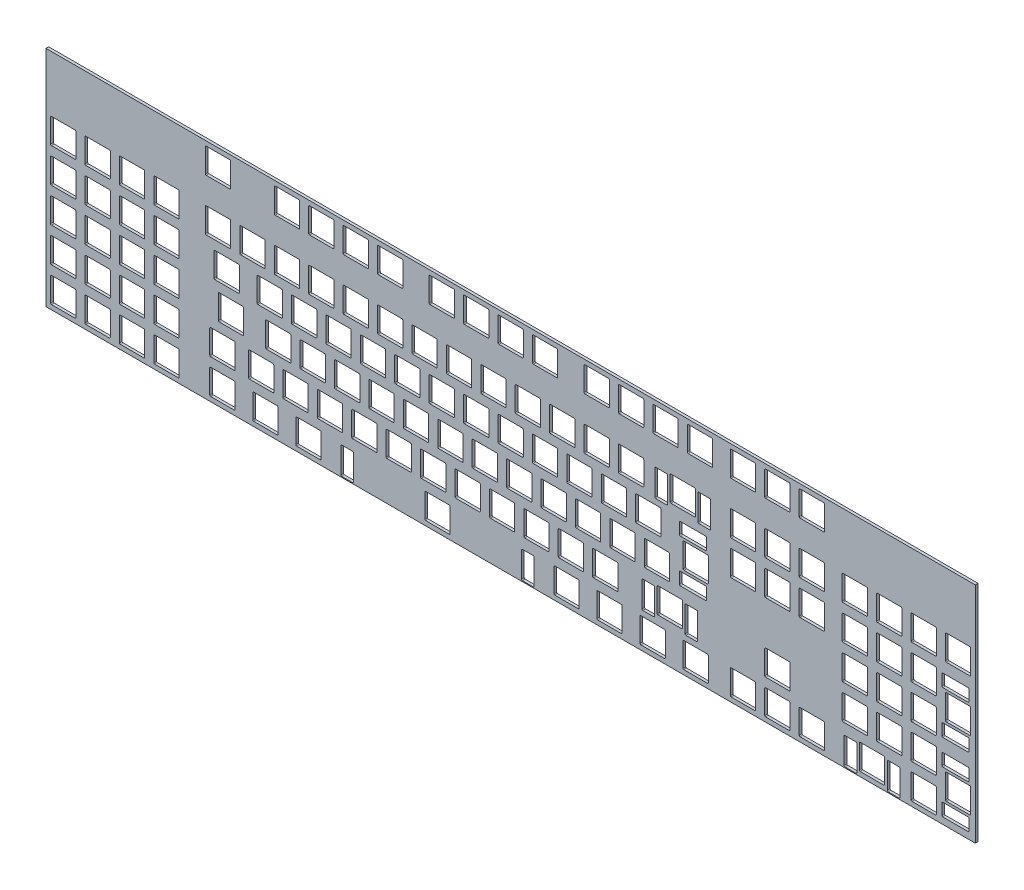
SolidWorks part; units mm, degrees
ref_plane "Front Plane" through (0, 0, 0) normal (0, 0, 1) x (1, 0, 0)
ref_plane "Top Plane" through (0, 0, 0) normal (0, 1, 0) x (1, 0, 0)
ref_plane "Right Plane" through (0, 0, 0) normal (1, 0, 0) x (0, 0, -1)
sketch "Model" plane through (0, 0, 0) normal (0, 0, 1) x (1, 0, 0)
  line L0 (88.75, -2.525) -> (101.75, -2.525)
  line L1 (88.75, -16.525) -> (101.75, -16.525)
  line L2 (88.25, -3.025) -> (88.25, -16.025)
  line L3 (102.25, -3.025) -> (102.25, -16.025)
  line L4 (126.85, -2.525) -> (139.85, -2.525)
  line L5 (126.85, -16.525) -> (139.85, -16.525)
  line L6 (126.35, -3.025) -> (126.35, -16.025)
  line L7 (140.35, -3.025) -> (140.35, -16.025)
  line L8 (145.9, -2.525) -> (158.9, -2.525)
  line L9 (145.9, -16.525) -> (158.9, -16.525)
  line L10 (145.4, -3.025) -> (145.4, -16.025)
  line L11 (159.4, -3.025) -> (159.4, -16.025)
  line L12 (164.95, -2.525) -> (177.95, -2.525)
  line L13 (164.95, -16.525) -> (177.95, -16.525)
  line L14 (164.45, -3.025) -> (164.45, -16.025)
  line L15 (178.45, -3.025) -> (178.45, -16.025)
  line L16 (184, -2.525) -> (197, -2.525)
  line L17 (184, -16.525) -> (197, -16.525)
  line L18 (183.5, -3.025) -> (183.5, -16.025)
  line L19 (197.5, -3.025) -> (197.5, -16.025)
  line L20 (212.575, -2.525) -> (225.575, -2.525)
  line L21 (212.575, -16.525) -> (225.575, -16.525)
  line L22 (212.075, -3.025) -> (212.075, -16.025)
  line L23 (226.075, -3.025) -> (226.075, -16.025)
  line L24 (231.625, -2.525) -> (244.625, -2.525)
  line L25 (231.625, -16.525) -> (244.625, -16.525)
  line L26 (231.125, -3.025) -> (231.125, -16.025)
  line L27 (245.125, -3.025) -> (245.125, -16.025)
  line L28 (250.675, -2.525) -> (263.675, -2.525)
  line L29 (250.675, -16.525) -> (263.675, -16.525)
  line L30 (250.175, -3.025) -> (250.175, -16.025)
  line L31 (264.175, -3.025) -> (264.175, -16.025)
  line L32 (269.725, -2.525) -> (282.725, -2.525)
  line L33 (269.725, -16.525) -> (282.725, -16.525)
  line L34 (269.225, -3.025) -> (269.225, -16.025)
  line L35 (283.225, -3.025) -> (283.225, -16.025)
  line L36 (298.3, -2.525) -> (311.3, -2.525)
  line L37 (298.3, -16.525) -> (311.3, -16.525)
  line L38 (297.8, -3.025) -> (297.8, -16.025)
  line L39 (311.8, -3.025) -> (311.8, -16.025)
  line L40 (317.35, -2.525) -> (330.35, -2.525)
  line L41 (317.35, -16.525) -> (330.35, -16.525)
  line L42 (316.85, -3.025) -> (316.85, -16.025)
  line L43 (330.85, -3.025) -> (330.85, -16.025)
  line L44 (336.4, -2.525) -> (349.4, -2.525)
  line L45 (336.4, -16.525) -> (349.4, -16.525)
  line L46 (335.9, -3.025) -> (335.9, -16.025)
  line L47 (349.9, -3.025) -> (349.9, -16.025)
  line L48 (355.45, -2.525) -> (368.45, -2.525)
  line L49 (355.45, -16.525) -> (368.45, -16.525)
  line L50 (354.95, -3.025) -> (354.95, -16.025)
  line L51 (368.95, -3.025) -> (368.95, -16.025)
  line L52 (379.2625, -2.525) -> (392.2625, -2.525)
  line L53 (379.2625, -16.525) -> (392.2625, -16.525)
  line L54 (378.7625, -3.025) -> (378.7625, -16.025)
  line L55 (392.7625, -3.025) -> (392.7625, -16.025)
  line L56 (398.3125, -2.525) -> (411.3125, -2.525)
  line L57 (398.3125, -16.525) -> (411.3125, -16.525)
  line L58 (397.8125, -3.025) -> (397.8125, -16.025)
  line L59 (411.8125, -3.025) -> (411.8125, -16.025)
  line L60 (417.3625, -2.525) -> (430.3625, -2.525)
  line L61 (417.3625, -16.525) -> (430.3625, -16.525)
  line L62 (416.8625, -3.025) -> (416.8625, -16.025)
  line L63 (430.8625, -3.025) -> (430.8625, -16.025)
  line L64 (3.025, -31.1) -> (16.025, -31.1)
  line L65 (3.025, -45.1) -> (16.025, -45.1)
  line L66 (2.525, -31.6) -> (2.525, -44.6)
  line L67 (16.525, -31.6) -> (16.525, -44.6)
  line L68 (22.075, -31.1) -> (35.075, -31.1)
  line L69 (22.075, -45.1) -> (35.075, -45.1)
  line L70 (21.575, -31.6) -> (21.575, -44.6)
  line L71 (35.575, -31.6) -> (35.575, -44.6)
  line L72 (41.125, -31.1) -> (54.125, -31.1)
  line L73 (41.125, -45.1) -> (54.125, -45.1)
  line L74 (40.625, -31.6) -> (40.625, -44.6)
  line L75 (54.625, -31.6) -> (54.625, -44.6)
  line L76 (60.175, -31.1) -> (73.175, -31.1)
  line L77 (60.175, -45.1) -> (73.175, -45.1)
  line L78 (59.675, -31.6) -> (59.675, -44.6)
  line L79 (73.675, -31.6) -> (73.675, -44.6)
  line L80 (88.75, -31.1) -> (101.75, -31.1)
  line L81 (88.75, -45.1) -> (101.75, -45.1)
  line L82 (88.25, -31.6) -> (88.25, -44.6)
  line L83 (102.25, -31.6) -> (102.25, -44.6)
  line L84 (107.8, -31.1) -> (120.8, -31.1)
  line L85 (107.8, -45.1) -> (120.8, -45.1)
  line L86 (107.3, -31.6) -> (107.3, -44.6)
  line L87 (121.3, -31.6) -> (121.3, -44.6)
  line L88 (126.85, -31.1) -> (139.85, -31.1)
  line L89 (126.85, -45.1) -> (139.85, -45.1)
  line L90 (126.35, -31.6) -> (126.35, -44.6)
  line L91 (140.35, -31.6) -> (140.35, -44.6)
  line L92 (145.9, -31.1) -> (158.9, -31.1)
  line L93 (145.9, -45.1) -> (158.9, -45.1)
  line L94 (145.4, -31.6) -> (145.4, -44.6)
  line L95 (159.4, -31.6) -> (159.4, -44.6)
  line L96 (164.95, -31.1) -> (177.95, -31.1)
  line L97 (164.95, -45.1) -> (177.95, -45.1)
  line L98 (164.45, -31.6) -> (164.45, -44.6)
  line L99 (178.45, -31.6) -> (178.45, -44.6)
  line L100 (184, -31.1) -> (197, -31.1)
  line L101 (184, -45.1) -> (197, -45.1)
  line L102 (183.5, -31.6) -> (183.5, -44.6)
  line L103 (197.5, -31.6) -> (197.5, -44.6)
  line L104 (203.05, -31.1) -> (216.05, -31.1)
  line L105 (203.05, -45.1) -> (216.05, -45.1)
  line L106 (202.55, -31.6) -> (202.55, -44.6)
  line L107 (216.55, -31.6) -> (216.55, -44.6)
  line L108 (222.1, -31.1) -> (235.1, -31.1)
  line L109 (222.1, -45.1) -> (235.1, -45.1)
  line L110 (221.6, -31.6) -> (221.6, -44.6)
  line L111 (235.6, -31.6) -> (235.6, -44.6)
  line L112 (241.15, -31.1) -> (254.15, -31.1)
  line L113 (241.15, -45.1) -> (254.15, -45.1)
  line L114 (240.65, -31.6) -> (240.65, -44.6)
  line L115 (254.65, -31.6) -> (254.65, -44.6)
  line L116 (260.2, -31.1) -> (273.2, -31.1)
  line L117 (260.2, -45.1) -> (273.2, -45.1)
  line L118 (259.7, -31.6) -> (259.7, -44.6)
  line L119 (273.7, -31.6) -> (273.7, -44.6)
  line L120 (279.25, -31.1) -> (292.25, -31.1)
  line L121 (279.25, -45.1) -> (292.25, -45.1)
  line L122 (278.75, -31.6) -> (278.75, -44.6)
  line L123 (292.75, -31.6) -> (292.75, -44.6)
  line L124 (298.3, -31.1) -> (311.3, -31.1)
  line L125 (298.3, -45.1) -> (311.3, -45.1)
  line L126 (297.8, -31.6) -> (297.8, -44.6)
  line L127 (311.8, -31.6) -> (311.8, -44.6)
  line L128 (317.35, -31.1) -> (330.35, -31.1)
  line L129 (317.35, -45.1) -> (330.35, -45.1)
  line L130 (316.85, -31.6) -> (316.85, -44.6)
  line L131 (330.85, -31.6) -> (330.85, -44.6)
  line L132 (345.925, -31.1) -> (358.925, -31.1)
  line L133 (345.925, -45.1) -> (358.925, -45.1)
  line L134 (345.425, -31.6) -> (345.425, -44.6)
  line L135 (359.425, -31.6) -> (359.425, -44.6)
  line L136 (337.487, -32.1) -> (343.487, -32.1)
  line L137 (337.487, -47.1) -> (343.487, -47.1)
  line L138 (336.987, -32.6) -> (336.987, -46.6)
  line L139 (343.987, -32.6) -> (343.987, -46.6)
  line L140 (361.363, -32.1) -> (367.363, -32.1)
  line L141 (361.363, -47.1) -> (367.363, -47.1)
  line L142 (360.863, -32.6) -> (360.863, -46.6)
  line L143 (367.863, -32.6) -> (367.863, -46.6)
  line L144 (379.2625, -31.1) -> (392.2625, -31.1)
  line L145 (379.2625, -45.1) -> (392.2625, -45.1)
  line L146 (378.7625, -31.6) -> (378.7625, -44.6)
  line L147 (392.7625, -31.6) -> (392.7625, -44.6)
  line L148 (398.3125, -31.1) -> (411.3125, -31.1)
  line L149 (398.3125, -45.1) -> (411.3125, -45.1)
  line L150 (397.8125, -31.6) -> (397.8125, -44.6)
  line L151 (411.8125, -31.6) -> (411.8125, -44.6)
  line L152 (417.3625, -31.1) -> (430.3625, -31.1)
  line L153 (417.3625, -45.1) -> (430.3625, -45.1)
  line L154 (416.8625, -31.6) -> (416.8625, -44.6)
  line L155 (430.8625, -31.6) -> (430.8625, -44.6)
  line L156 (441.175, -31.1) -> (454.175, -31.1)
  line L157 (441.175, -45.1) -> (454.175, -45.1)
  line L158 (440.675, -31.6) -> (440.675, -44.6)
  line L159 (454.675, -31.6) -> (454.675, -44.6)
  line L160 (460.225, -31.1) -> (473.225, -31.1)
  line L161 (460.225, -45.1) -> (473.225, -45.1)
  line L162 (459.725, -31.6) -> (459.725, -44.6)
  line L163 (473.725, -31.6) -> (473.725, -44.6)
  line L164 (479.275, -31.1) -> (492.275, -31.1)
  line L165 (479.275, -45.1) -> (492.275, -45.1)
  line L166 (478.775, -31.6) -> (478.775, -44.6)
  line L167 (492.775, -31.6) -> (492.775, -44.6)
  line L168 (498.325, -31.1) -> (511.325, -31.1)
  line L169 (498.325, -45.1) -> (511.325, -45.1)
  line L170 (497.825, -31.6) -> (497.825, -44.6)
  line L171 (511.825, -31.6) -> (511.825, -44.6)
  line L172 (3.025, -50.15) -> (16.025, -50.15)
  line L173 (3.025, -64.15) -> (16.025, -64.15)
  line L174 (2.525, -50.65) -> (2.525, -63.65)
  line L175 (16.525, -50.65) -> (16.525, -63.65)
  line L176 (22.075, -50.15) -> (35.075, -50.15)
  line L177 (22.075, -64.15) -> (35.075, -64.15)
  line L178 (21.575, -50.65) -> (21.575, -63.65)
  line L179 (35.575, -50.65) -> (35.575, -63.65)
  line L180 (41.125, -50.15) -> (54.125, -50.15)
  line L181 (41.125, -64.15) -> (54.125, -64.15)
  line L182 (40.625, -50.65) -> (40.625, -63.65)
  line L183 (54.625, -50.65) -> (54.625, -63.65)
  line L184 (60.175, -50.15) -> (73.175, -50.15)
  line L185 (60.175, -64.15) -> (73.175, -64.15)
  line L186 (59.675, -50.65) -> (59.675, -63.65)
  line L187 (73.675, -50.65) -> (73.675, -63.65)
  line L188 (93.5125, -50.15) -> (106.5125, -50.15)
  line L189 (93.5125, -64.15) -> (106.5125, -64.15)
  line L190 (93.0125, -50.65) -> (93.0125, -63.65)
  line L191 (107.0125, -50.65) -> (107.0125, -63.65)
  line L192 (117.325, -50.15) -> (130.325, -50.15)
  line L193 (117.325, -64.15) -> (130.325, -64.15)
  line L194 (116.825, -50.65) -> (116.825, -63.65)
  line L195 (130.825, -50.65) -> (130.825, -63.65)
  line L196 (136.375, -50.15) -> (149.375, -50.15)
  line L197 (136.375, -64.15) -> (149.375, -64.15)
  line L198 (135.875, -50.65) -> (135.875, -63.65)
  line L199 (149.875, -50.65) -> (149.875, -63.65)
  line L200 (155.425, -50.15) -> (168.425, -50.15)
  line L201 (155.425, -64.15) -> (168.425, -64.15)
  line L202 (154.925, -50.65) -> (154.925, -63.65)
  line L203 (168.925, -50.65) -> (168.925, -63.65)
  line L204 (174.475, -50.15) -> (187.475, -50.15)
  line L205 (174.475, -64.15) -> (187.475, -64.15)
  line L206 (173.975, -50.65) -> (173.975, -63.65)
  line L207 (187.975, -50.65) -> (187.975, -63.65)
  line L208 (193.525, -50.15) -> (206.525, -50.15)
  line L209 (193.525, -64.15) -> (206.525, -64.15)
  line L210 (193.025, -50.65) -> (193.025, -63.65)
  line L211 (207.025, -50.65) -> (207.025, -63.65)
  line L212 (212.575, -50.15) -> (225.575, -50.15)
  line L213 (212.575, -64.15) -> (225.575, -64.15)
  line L214 (212.075, -50.65) -> (212.075, -63.65)
  line L215 (226.075, -50.65) -> (226.075, -63.65)
  line L216 (231.625, -50.15) -> (244.625, -50.15)
  line L217 (231.625, -64.15) -> (244.625, -64.15)
  line L218 (231.125, -50.65) -> (231.125, -63.65)
  line L219 (245.125, -50.65) -> (245.125, -63.65)
  line L220 (250.675, -50.15) -> (263.675, -50.15)
  line L221 (250.675, -64.15) -> (263.675, -64.15)
  line L222 (250.175, -50.65) -> (250.175, -63.65)
  line L223 (264.175, -50.65) -> (264.175, -63.65)
  line L224 (269.725, -50.15) -> (282.725, -50.15)
  line L225 (269.725, -64.15) -> (282.725, -64.15)
  line L226 (269.225, -50.65) -> (269.225, -63.65)
  line L227 (283.225, -50.65) -> (283.225, -63.65)
  line L228 (288.775, -50.15) -> (301.775, -50.15)
  line L229 (288.775, -64.15) -> (301.775, -64.15)
  line L230 (288.275, -50.65) -> (288.275, -63.65)
  line L231 (302.275, -50.65) -> (302.275, -63.65)
  line L232 (307.825, -50.15) -> (320.825, -50.15)
  line L233 (307.825, -64.15) -> (320.825, -64.15)
  line L234 (307.325, -50.65) -> (307.325, -63.65)
  line L235 (321.325, -50.65) -> (321.325, -63.65)
  line L236 (326.875, -50.15) -> (339.875, -50.15)
  line L237 (326.875, -64.15) -> (339.875, -64.15)
  line L238 (326.375, -50.65) -> (326.375, -63.65)
  line L239 (340.375, -50.65) -> (340.375, -63.65)
  line L240 (366.5688, -60.175) -> (366.5688, -73.175)
  line L241 (352.5688, -60.175) -> (352.5688, -73.175)
  line L242 (366.0688, -59.675) -> (353.0688, -59.675)
  line L243 (366.0688, -73.675) -> (353.0688, -73.675)
  line L244 (365.5688, -51.737) -> (365.5688, -57.737)
  line L245 (350.5688, -51.737) -> (350.5688, -57.737)
  line L246 (365.0688, -51.237) -> (351.0688, -51.237)
  line L247 (365.0688, -58.237) -> (351.0688, -58.237)
  line L248 (365.5688, -75.613) -> (365.5688, -81.613)
  line L249 (350.5688, -75.613) -> (350.5688, -81.613)
  line L250 (365.0688, -75.113) -> (351.0688, -75.113)
  line L251 (365.0688, -82.113) -> (351.0688, -82.113)
  line L252 (379.2625, -50.15) -> (392.2625, -50.15)
  line L253 (379.2625, -64.15) -> (392.2625, -64.15)
  line L254 (378.7625, -50.65) -> (378.7625, -63.65)
  line L255 (392.7625, -50.65) -> (392.7625, -63.65)
  line L256 (398.3125, -50.15) -> (411.3125, -50.15)
  line L257 (398.3125, -64.15) -> (411.3125, -64.15)
  line L258 (397.8125, -50.65) -> (397.8125, -63.65)
  line L259 (411.8125, -50.65) -> (411.8125, -63.65)
  line L260 (417.3625, -50.15) -> (430.3625, -50.15)
  line L261 (417.3625, -64.15) -> (430.3625, -64.15)
  line L262 (416.8625, -50.65) -> (416.8625, -63.65)
  line L263 (430.8625, -50.65) -> (430.8625, -63.65)
  line L264 (441.175, -50.15) -> (454.175, -50.15)
  line L265 (441.175, -64.15) -> (454.175, -64.15)
  line L266 (440.675, -50.65) -> (440.675, -63.65)
  line L267 (454.675, -50.65) -> (454.675, -63.65)
  line L268 (460.225, -50.15) -> (473.225, -50.15)
  line L269 (460.225, -64.15) -> (473.225, -64.15)
  line L270 (459.725, -50.65) -> (459.725, -63.65)
  line L271 (473.725, -50.65) -> (473.725, -63.65)
  line L272 (479.275, -50.15) -> (492.275, -50.15)
  line L273 (479.275, -64.15) -> (492.275, -64.15)
  line L274 (478.775, -50.65) -> (478.775, -63.65)
  line L275 (492.775, -50.65) -> (492.775, -63.65)
  line L276 (511.825, -60.175) -> (511.825, -73.175)
  line L277 (497.825, -60.175) -> (497.825, -73.175)
  line L278 (511.325, -59.675) -> (498.325, -59.675)
  line L279 (511.325, -73.675) -> (498.325, -73.675)
  line L280 (510.825, -51.737) -> (510.825, -57.737)
  line L281 (495.825, -51.737) -> (495.825, -57.737)
  line L282 (510.325, -51.237) -> (496.325, -51.237)
  line L283 (510.325, -58.237) -> (496.325, -58.237)
  line L284 (510.825, -75.613) -> (510.825, -81.613)
  line L285 (495.825, -75.613) -> (495.825, -81.613)
  line L286 (510.325, -75.113) -> (496.325, -75.113)
  line L287 (510.325, -82.113) -> (496.325, -82.113)
  line L288 (3.025, -69.2) -> (16.025, -69.2)
  line L289 (3.025, -83.2) -> (16.025, -83.2)
  line L290 (2.525, -69.7) -> (2.525, -82.7)
  line L291 (16.525, -69.7) -> (16.525, -82.7)
  line L292 (22.075, -69.2) -> (35.075, -69.2)
  line L293 (22.075, -83.2) -> (35.075, -83.2)
  line L294 (21.575, -69.7) -> (21.575, -82.7)
  line L295 (35.575, -69.7) -> (35.575, -82.7)
  line L296 (41.125, -69.2) -> (54.125, -69.2)
  line L297 (41.125, -83.2) -> (54.125, -83.2)
  line L298 (40.625, -69.7) -> (40.625, -82.7)
  line L299 (54.625, -69.7) -> (54.625, -82.7)
  line L300 (60.175, -69.2) -> (73.175, -69.2)
  line L301 (60.175, -83.2) -> (73.175, -83.2)
  line L302 (59.675, -69.7) -> (59.675, -82.7)
  line L303 (73.675, -69.7) -> (73.675, -82.7)
  line L304 (95.8937, -69.2) -> (108.8937, -69.2)
  line L305 (95.8937, -83.2) -> (108.8937, -83.2)
  line L306 (95.3937, -69.7) -> (95.3937, -82.7)
  line L307 (109.3937, -69.7) -> (109.3937, -82.7)
  line L308 (122.0875, -69.2) -> (135.0875, -69.2)
  line L309 (122.0875, -83.2) -> (135.0875, -83.2)
  line L310 (121.5875, -69.7) -> (121.5875, -82.7)
  line L311 (135.5875, -69.7) -> (135.5875, -82.7)
  line L312 (141.1375, -69.2) -> (154.1375, -69.2)
  line L313 (141.1375, -83.2) -> (154.1375, -83.2)
  line L314 (140.6375, -69.7) -> (140.6375, -82.7)
  line L315 (154.6375, -69.7) -> (154.6375, -82.7)
  line L316 (160.1875, -69.2) -> (173.1875, -69.2)
  line L317 (160.1875, -83.2) -> (173.1875, -83.2)
  line L318 (159.6875, -69.7) -> (159.6875, -82.7)
  line L319 (173.6875, -69.7) -> (173.6875, -82.7)
  line L320 (179.2375, -69.2) -> (192.2375, -69.2)
  line L321 (179.2375, -83.2) -> (192.2375, -83.2)
  line L322 (178.7375, -69.7) -> (178.7375, -82.7)
  line L323 (192.7375, -69.7) -> (192.7375, -82.7)
  line L324 (198.2875, -69.2) -> (211.2875, -69.2)
  line L325 (198.2875, -83.2) -> (211.2875, -83.2)
  line L326 (197.7875, -69.7) -> (197.7875, -82.7)
  line L327 (211.7875, -69.7) -> (211.7875, -82.7)
  line L328 (217.3375, -69.2) -> (230.3375, -69.2)
  line L329 (217.3375, -83.2) -> (230.3375, -83.2)
  line L330 (216.8375, -69.7) -> (216.8375, -82.7)
  line L331 (230.8375, -69.7) -> (230.8375, -82.7)
  line L332 (236.3875, -69.2) -> (249.3875, -69.2)
  line L333 (236.3875, -83.2) -> (249.3875, -83.2)
  line L334 (235.8875, -69.7) -> (235.8875, -82.7)
  line L335 (249.8875, -69.7) -> (249.8875, -82.7)
  line L336 (255.4375, -69.2) -> (268.4375, -69.2)
  line L337 (255.4375, -83.2) -> (268.4375, -83.2)
  line L338 (254.9375, -69.7) -> (254.9375, -82.7)
  line L339 (268.9375, -69.7) -> (268.9375, -82.7)
  line L340 (274.4875, -69.2) -> (287.4875, -69.2)
  line L341 (274.4875, -83.2) -> (287.4875, -83.2)
  line L342 (273.9875, -69.7) -> (273.9875, -82.7)
  line L343 (287.9875, -69.7) -> (287.9875, -82.7)
  line L344 (293.5375, -69.2) -> (306.5375, -69.2)
  line L345 (293.5375, -83.2) -> (306.5375, -83.2)
  line L346 (293.0375, -69.7) -> (293.0375, -82.7)
  line L347 (307.0375, -69.7) -> (307.0375, -82.7)
  line L348 (312.5875, -69.2) -> (325.5875, -69.2)
  line L349 (312.5875, -83.2) -> (325.5875, -83.2)
  line L350 (312.0875, -69.7) -> (312.0875, -82.7)
  line L351 (326.0875, -69.7) -> (326.0875, -82.7)
  line L352 (331.6375, -69.2) -> (344.6375, -69.2)
  line L353 (331.6375, -83.2) -> (344.6375, -83.2)
  line L354 (331.1375, -69.7) -> (331.1375, -82.7)
  line L355 (345.1375, -69.7) -> (345.1375, -82.7)
  line L356 (441.175, -69.2) -> (454.175, -69.2)
  line L357 (441.175, -83.2) -> (454.175, -83.2)
  line L358 (440.675, -69.7) -> (440.675, -82.7)
  line L359 (454.675, -69.7) -> (454.675, -82.7)
  line L360 (460.225, -69.2) -> (473.225, -69.2)
  line L361 (460.225, -83.2) -> (473.225, -83.2)
  line L362 (459.725, -69.7) -> (459.725, -82.7)
  line L363 (473.725, -69.7) -> (473.725, -82.7)
  line L364 (479.275, -69.2) -> (492.275, -69.2)
  line L365 (479.275, -83.2) -> (492.275, -83.2)
  line L366 (478.775, -69.7) -> (478.775, -82.7)
  line L367 (492.775, -69.7) -> (492.775, -82.7)
  line L368 (3.025, -88.25) -> (16.025, -88.25)
  line L369 (3.025, -102.25) -> (16.025, -102.25)
  line L370 (2.525, -88.75) -> (2.525, -101.75)
  line L371 (16.525, -88.75) -> (16.525, -101.75)
  line L372 (22.075, -88.25) -> (35.075, -88.25)
  line L373 (22.075, -102.25) -> (35.075, -102.25)
  line L374 (21.575, -88.75) -> (21.575, -101.75)
  line L375 (35.575, -88.75) -> (35.575, -101.75)
  line L376 (41.125, -88.25) -> (54.125, -88.25)
  line L377 (41.125, -102.25) -> (54.125, -102.25)
  line L378 (40.625, -88.75) -> (40.625, -101.75)
  line L379 (54.625, -88.75) -> (54.625, -101.75)
  line L380 (60.175, -88.25) -> (73.175, -88.25)
  line L381 (60.175, -102.25) -> (73.175, -102.25)
  line L382 (59.675, -88.75) -> (59.675, -101.75)
  line L383 (73.675, -88.75) -> (73.675, -101.75)
  line L384 (91.1312, -88.25) -> (104.1312, -88.25)
  line L385 (91.1312, -102.25) -> (104.1312, -102.25)
  line L386 (90.6312, -88.75) -> (90.6312, -101.75)
  line L387 (104.6312, -88.75) -> (104.6312, -101.75)
  line L388 (112.5625, -88.25) -> (125.5625, -88.25)
  line L389 (112.5625, -102.25) -> (125.5625, -102.25)
  line L390 (112.0625, -88.75) -> (112.0625, -101.75)
  line L391 (126.0625, -88.75) -> (126.0625, -101.75)
  line L392 (131.6125, -88.25) -> (144.6125, -88.25)
  line L393 (131.6125, -102.25) -> (144.6125, -102.25)
  line L394 (131.1125, -88.75) -> (131.1125, -101.75)
  line L395 (145.1125, -88.75) -> (145.1125, -101.75)
  line L396 (150.6625, -88.25) -> (163.6625, -88.25)
  line L397 (150.6625, -102.25) -> (163.6625, -102.25)
  line L398 (150.1625, -88.75) -> (150.1625, -101.75)
  line L399 (164.1625, -88.75) -> (164.1625, -101.75)
  line L400 (169.7125, -88.25) -> (182.7125, -88.25)
  line L401 (169.7125, -102.25) -> (182.7125, -102.25)
  line L402 (169.2125, -88.75) -> (169.2125, -101.75)
  line L403 (183.2125, -88.75) -> (183.2125, -101.75)
  line L404 (188.7625, -88.25) -> (201.7625, -88.25)
  line L405 (188.7625, -102.25) -> (201.7625, -102.25)
  line L406 (188.2625, -88.75) -> (188.2625, -101.75)
  line L407 (202.2625, -88.75) -> (202.2625, -101.75)
  line L408 (207.8125, -88.25) -> (220.8125, -88.25)
  line L409 (207.8125, -102.25) -> (220.8125, -102.25)
  line L410 (207.3125, -88.75) -> (207.3125, -101.75)
  line L411 (221.3125, -88.75) -> (221.3125, -101.75)
  line L412 (226.8625, -88.25) -> (239.8625, -88.25)
  line L413 (226.8625, -102.25) -> (239.8625, -102.25)
  line L414 (226.3625, -88.75) -> (226.3625, -101.75)
  line L415 (240.3625, -88.75) -> (240.3625, -101.75)
  line L416 (245.9125, -88.25) -> (258.9125, -88.25)
  line L417 (245.9125, -102.25) -> (258.9125, -102.25)
  line L418 (245.4125, -88.75) -> (245.4125, -101.75)
  line L419 (259.4125, -88.75) -> (259.4125, -101.75)
  line L420 (264.9625, -88.25) -> (277.9625, -88.25)
  line L421 (264.9625, -102.25) -> (277.9625, -102.25)
  line L422 (264.4625, -88.75) -> (264.4625, -101.75)
  line L423 (278.4625, -88.75) -> (278.4625, -101.75)
  line L424 (284.0125, -88.25) -> (297.0125, -88.25)
  line L425 (284.0125, -102.25) -> (297.0125, -102.25)
  line L426 (283.5125, -88.75) -> (283.5125, -101.75)
  line L427 (297.5125, -88.75) -> (297.5125, -101.75)
  line L428 (303.0625, -88.25) -> (316.0625, -88.25)
  line L429 (303.0625, -102.25) -> (316.0625, -102.25)
  line L430 (302.5625, -88.75) -> (302.5625, -101.75)
  line L431 (316.5625, -88.75) -> (316.5625, -101.75)
  line L432 (338.7813, -88.25) -> (351.7812, -88.25)
  line L433 (338.7813, -102.25) -> (351.7812, -102.25)
  line L434 (338.2813, -88.75) -> (338.2813, -101.75)
  line L435 (352.2812, -88.75) -> (352.2812, -101.75)
  line L436 (330.3433, -89.25) -> (336.3433, -89.25)
  line L437 (330.3433, -104.25) -> (336.3433, -104.25)
  line L438 (329.8433, -89.75) -> (329.8433, -103.75)
  line L439 (336.8433, -89.75) -> (336.8433, -103.75)
  line L440 (354.2192, -89.25) -> (360.2192, -89.25)
  line L441 (354.2192, -104.25) -> (360.2192, -104.25)
  line L442 (353.7192, -89.75) -> (353.7192, -103.75)
  line L443 (360.7192, -89.75) -> (360.7192, -103.75)
  line L444 (398.3125, -88.25) -> (411.3125, -88.25)
  line L445 (398.3125, -102.25) -> (411.3125, -102.25)
  line L446 (397.8125, -88.75) -> (397.8125, -101.75)
  line L447 (411.8125, -88.75) -> (411.8125, -101.75)
  line L448 (441.175, -88.25) -> (454.175, -88.25)
  line L449 (441.175, -102.25) -> (454.175, -102.25)
  line L450 (440.675, -88.75) -> (440.675, -101.75)
  line L451 (454.675, -88.75) -> (454.675, -101.75)
  line L452 (460.225, -88.25) -> (473.225, -88.25)
  line L453 (460.225, -102.25) -> (473.225, -102.25)
  line L454 (459.725, -88.75) -> (459.725, -101.75)
  line L455 (473.725, -88.75) -> (473.725, -101.75)
  line L456 (479.275, -88.25) -> (492.275, -88.25)
  line L457 (479.275, -102.25) -> (492.275, -102.25)
  line L458 (478.775, -88.75) -> (478.775, -101.75)
  line L459 (492.775, -88.75) -> (492.775, -101.75)
  line L460 (511.825, -98.275) -> (511.825, -111.275)
  line L461 (497.825, -98.275) -> (497.825, -111.275)
  line L462 (511.325, -97.775) -> (498.325, -97.775)
  line L463 (511.325, -111.775) -> (498.325, -111.775)
  line L464 (510.825, -89.837) -> (510.825, -95.837)
  line L465 (495.825, -89.837) -> (495.825, -95.837)
  line L466 (510.325, -89.337) -> (496.325, -89.337)
  line L467 (510.325, -96.337) -> (496.325, -96.337)
  line L468 (510.825, -113.713) -> (510.825, -119.713)
  line L469 (495.825, -113.713) -> (495.825, -119.713)
  line L470 (510.325, -113.213) -> (496.325, -113.213)
  line L471 (510.325, -120.213) -> (496.325, -120.213)
  line L472 (3.025, -107.3) -> (16.025, -107.3)
  line L473 (3.025, -121.3) -> (16.025, -121.3)
  line L474 (2.525, -107.8) -> (2.525, -120.8)
  line L475 (16.525, -107.8) -> (16.525, -120.8)
  line L476 (22.075, -107.3) -> (35.075, -107.3)
  line L477 (22.075, -121.3) -> (35.075, -121.3)
  line L478 (21.575, -107.8) -> (21.575, -120.8)
  line L479 (35.575, -107.8) -> (35.575, -120.8)
  line L480 (41.125, -107.3) -> (54.125, -107.3)
  line L481 (41.125, -121.3) -> (54.125, -121.3)
  line L482 (40.625, -107.8) -> (40.625, -120.8)
  line L483 (54.625, -107.8) -> (54.625, -120.8)
  line L484 (60.175, -107.3) -> (73.175, -107.3)
  line L485 (60.175, -121.3) -> (73.175, -121.3)
  line L486 (59.675, -107.8) -> (59.675, -120.8)
  line L487 (73.675, -107.8) -> (73.675, -120.8)
  line L488 (91.1312, -107.3) -> (104.1312, -107.3)
  line L489 (91.1312, -121.3) -> (104.1312, -121.3)
  line L490 (90.6312, -107.8) -> (90.6312, -120.8)
  line L491 (104.6312, -107.8) -> (104.6312, -120.8)
  line L492 (114.9437, -107.3) -> (127.9437, -107.3)
  line L493 (114.9437, -121.3) -> (127.9437, -121.3)
  line L494 (114.4437, -107.8) -> (114.4437, -120.8)
  line L495 (128.4437, -107.8) -> (128.4437, -120.8)
  line L496 (138.7562, -107.3) -> (151.7563, -107.3)
  line L497 (138.7562, -121.3) -> (151.7563, -121.3)
  line L498 (138.2562, -107.8) -> (138.2562, -120.8)
  line L499 (152.2563, -107.8) -> (152.2563, -120.8)
  line L500 (210.1938, -107.3) -> (223.1937, -107.3)
  line L501 (210.1938, -121.3) -> (223.1937, -121.3)
  line L502 (209.6938, -107.8) -> (209.6938, -120.8)
  line L503 (223.6937, -107.8) -> (223.6937, -120.8)
  line L504 (163.6937, -108.3) -> (169.6937, -108.3)
  line L505 (163.6937, -123.3) -> (169.6937, -123.3)
  line L506 (163.1937, -108.8) -> (163.1937, -122.8)
  line L507 (170.1937, -108.8) -> (170.1937, -122.8)
  line L508 (263.6938, -108.3) -> (269.6938, -108.3)
  line L509 (263.6938, -123.3) -> (269.6938, -123.3)
  line L510 (263.1938, -108.8) -> (263.1938, -122.8)
  line L511 (270.1938, -108.8) -> (270.1938, -122.8)
  line L512 (281.6313, -107.3) -> (294.6313, -107.3)
  line L513 (281.6313, -121.3) -> (294.6313, -121.3)
  line L514 (281.1313, -107.8) -> (281.1313, -120.8)
  line L515 (295.1313, -107.8) -> (295.1313, -120.8)
  line L516 (305.4438, -107.3) -> (318.4438, -107.3)
  line L517 (305.4438, -121.3) -> (318.4438, -121.3)
  line L518 (304.9438, -107.8) -> (304.9438, -120.8)
  line L519 (318.9438, -107.8) -> (318.9438, -120.8)
  line L520 (329.2563, -107.3) -> (342.2563, -107.3)
  line L521 (329.2563, -121.3) -> (342.2563, -121.3)
  line L522 (328.7563, -107.8) -> (328.7563, -120.8)
  line L523 (342.7563, -107.8) -> (342.7563, -120.8)
  line L524 (353.0688, -107.3) -> (366.0688, -107.3)
  line L525 (353.0688, -121.3) -> (366.0688, -121.3)
  line L526 (352.5688, -107.8) -> (352.5688, -120.8)
  line L527 (366.5688, -107.8) -> (366.5688, -120.8)
  line L528 (379.2625, -107.3) -> (392.2625, -107.3)
  line L529 (379.2625, -121.3) -> (392.2625, -121.3)
  line L530 (378.7625, -107.8) -> (378.7625, -120.8)
  line L531 (392.7625, -107.8) -> (392.7625, -120.8)
  line L532 (398.3125, -107.3) -> (411.3125, -107.3)
  line L533 (398.3125, -121.3) -> (411.3125, -121.3)
  line L534 (397.8125, -107.8) -> (397.8125, -120.8)
  line L535 (411.8125, -107.8) -> (411.8125, -120.8)
  line L536 (417.3625, -107.3) -> (430.3625, -107.3)
  line L537 (417.3625, -121.3) -> (430.3625, -121.3)
  line L538 (416.8625, -107.8) -> (416.8625, -120.8)
  line L539 (430.8625, -107.8) -> (430.8625, -120.8)
  line L540 (450.7, -107.3) -> (463.7, -107.3)
  line L541 (450.7, -121.3) -> (463.7, -121.3)
  line L542 (450.2, -107.8) -> (450.2, -120.8)
  line L543 (464.2, -107.8) -> (464.2, -120.8)
  line L544 (442.262, -108.3) -> (448.262, -108.3)
  line L545 (442.262, -123.3) -> (448.262, -123.3)
  line L546 (441.762, -108.8) -> (441.762, -122.8)
  line L547 (448.762, -108.8) -> (448.762, -122.8)
  line L548 (466.138, -108.3) -> (472.138, -108.3)
  line L549 (466.138, -123.3) -> (472.138, -123.3)
  line L550 (465.638, -108.8) -> (465.638, -122.8)
  line L551 (472.638, -108.8) -> (472.638, -122.8)
  line L552 (479.275, -107.3) -> (492.275, -107.3)
  line L553 (479.275, -121.3) -> (492.275, -121.3)
  line L554 (478.775, -107.8) -> (478.775, -120.8)
  line L555 (492.775, -107.8) -> (492.775, -120.8)
  line L556 (0, -123.825) -> (514.35, -123.825)
  line L557 (0, 0) -> (514.35, 0)
  line L558 (0, -123.825) -> (0, 0)
  line L559 (514.35, -123.825) -> (514.35, 0)
  arc A0 (88.75, -2.525) -> (88.25, -3.025) centre (88.75, -3.025) ccw
  arc A1 (102.25, -3.025) -> (101.75, -2.525) centre (101.75, -3.025) ccw
  arc A2 (88.25, -16.025) -> (88.75, -16.525) centre (88.75, -16.025) ccw
  arc A3 (101.75, -16.525) -> (102.25, -16.025) centre (101.75, -16.025) ccw
  arc A4 (126.85, -2.525) -> (126.35, -3.025) centre (126.85, -3.025) ccw
  arc A5 (140.35, -3.025) -> (139.85, -2.525) centre (139.85, -3.025) ccw
  arc A6 (126.35, -16.025) -> (126.85, -16.525) centre (126.85, -16.025) ccw
  arc A7 (139.85, -16.525) -> (140.35, -16.025) centre (139.85, -16.025) ccw
  arc A8 (145.9, -2.525) -> (145.4, -3.025) centre (145.9, -3.025) ccw
  arc A9 (159.4, -3.025) -> (158.9, -2.525) centre (158.9, -3.025) ccw
  arc A10 (145.4, -16.025) -> (145.9, -16.525) centre (145.9, -16.025) ccw
  arc A11 (158.9, -16.525) -> (159.4, -16.025) centre (158.9, -16.025) ccw
  arc A12 (164.95, -2.525) -> (164.45, -3.025) centre (164.95, -3.025) ccw
  arc A13 (178.45, -3.025) -> (177.95, -2.525) centre (177.95, -3.025) ccw
  arc A14 (164.45, -16.025) -> (164.95, -16.525) centre (164.95, -16.025) ccw
  arc A15 (177.95, -16.525) -> (178.45, -16.025) centre (177.95, -16.025) ccw
  arc A16 (184, -2.525) -> (183.5, -3.025) centre (184, -3.025) ccw
  arc A17 (197.5, -3.025) -> (197, -2.525) centre (197, -3.025) ccw
  arc A18 (183.5, -16.025) -> (184, -16.525) centre (184, -16.025) ccw
  arc A19 (197, -16.525) -> (197.5, -16.025) centre (197, -16.025) ccw
  arc A20 (212.575, -2.525) -> (212.075, -3.025) centre (212.575, -3.025) ccw
  arc A21 (226.075, -3.025) -> (225.575, -2.525) centre (225.575, -3.025) ccw
  arc A22 (212.075, -16.025) -> (212.575, -16.525) centre (212.575, -16.025) ccw
  arc A23 (225.575, -16.525) -> (226.075, -16.025) centre (225.575, -16.025) ccw
  arc A24 (231.625, -2.525) -> (231.125, -3.025) centre (231.625, -3.025) ccw
  arc A25 (245.125, -3.025) -> (244.625, -2.525) centre (244.625, -3.025) ccw
  arc A26 (231.125, -16.025) -> (231.625, -16.525) centre (231.625, -16.025) ccw
  arc A27 (244.625, -16.525) -> (245.125, -16.025) centre (244.625, -16.025) ccw
  arc A28 (250.675, -2.525) -> (250.175, -3.025) centre (250.675, -3.025) ccw
  arc A29 (264.175, -3.025) -> (263.675, -2.525) centre (263.675, -3.025) ccw
  arc A30 (250.175, -16.025) -> (250.675, -16.525) centre (250.675, -16.025) ccw
  arc A31 (263.675, -16.525) -> (264.175, -16.025) centre (263.675, -16.025) ccw
  arc A32 (269.725, -2.525) -> (269.225, -3.025) centre (269.725, -3.025) ccw
  arc A33 (283.225, -3.025) -> (282.725, -2.525) centre (282.725, -3.025) ccw
  arc A34 (269.225, -16.025) -> (269.725, -16.525) centre (269.725, -16.025) ccw
  arc A35 (282.725, -16.525) -> (283.225, -16.025) centre (282.725, -16.025) ccw
  arc A36 (298.3, -2.525) -> (297.8, -3.025) centre (298.3, -3.025) ccw
  arc A37 (311.8, -3.025) -> (311.3, -2.525) centre (311.3, -3.025) ccw
  arc A38 (297.8, -16.025) -> (298.3, -16.525) centre (298.3, -16.025) ccw
  arc A39 (311.3, -16.525) -> (311.8, -16.025) centre (311.3, -16.025) ccw
  arc A40 (317.35, -2.525) -> (316.85, -3.025) centre (317.35, -3.025) ccw
  arc A41 (330.85, -3.025) -> (330.35, -2.525) centre (330.35, -3.025) ccw
  arc A42 (316.85, -16.025) -> (317.35, -16.525) centre (317.35, -16.025) ccw
  arc A43 (330.35, -16.525) -> (330.85, -16.025) centre (330.35, -16.025) ccw
  arc A44 (336.4, -2.525) -> (335.9, -3.025) centre (336.4, -3.025) ccw
  arc A45 (349.9, -3.025) -> (349.4, -2.525) centre (349.4, -3.025) ccw
  arc A46 (335.9, -16.025) -> (336.4, -16.525) centre (336.4, -16.025) ccw
  arc A47 (349.4, -16.525) -> (349.9, -16.025) centre (349.4, -16.025) ccw
  arc A48 (355.45, -2.525) -> (354.95, -3.025) centre (355.45, -3.025) ccw
  arc A49 (368.95, -3.025) -> (368.45, -2.525) centre (368.45, -3.025) ccw
  arc A50 (354.95, -16.025) -> (355.45, -16.525) centre (355.45, -16.025) ccw
  arc A51 (368.45, -16.525) -> (368.95, -16.025) centre (368.45, -16.025) ccw
  arc A52 (379.2625, -2.525) -> (378.7625, -3.025) centre (379.2625, -3.025) ccw
  arc A53 (392.7625, -3.025) -> (392.2625, -2.525) centre (392.2625, -3.025) ccw
  arc A54 (378.7625, -16.025) -> (379.2625, -16.525) centre (379.2625, -16.025) ccw
  arc A55 (392.2625, -16.525) -> (392.7625, -16.025) centre (392.2625, -16.025) ccw
  arc A56 (398.3125, -2.525) -> (397.8125, -3.025) centre (398.3125, -3.025) ccw
  arc A57 (411.8125, -3.025) -> (411.3125, -2.525) centre (411.3125, -3.025) ccw
  arc A58 (397.8125, -16.025) -> (398.3125, -16.525) centre (398.3125, -16.025) ccw
  arc A59 (411.3125, -16.525) -> (411.8125, -16.025) centre (411.3125, -16.025) ccw
  arc A60 (417.3625, -2.525) -> (416.8625, -3.025) centre (417.3625, -3.025) ccw
  arc A61 (430.8625, -3.025) -> (430.3625, -2.525) centre (430.3625, -3.025) ccw
  arc A62 (416.8625, -16.025) -> (417.3625, -16.525) centre (417.3625, -16.025) ccw
  arc A63 (430.3625, -16.525) -> (430.8625, -16.025) centre (430.3625, -16.025) ccw
  arc A64 (3.025, -31.1) -> (2.525, -31.6) centre (3.025, -31.6) ccw
  arc A65 (16.525, -31.6) -> (16.025, -31.1) centre (16.025, -31.6) ccw
  arc A66 (2.525, -44.6) -> (3.025, -45.1) centre (3.025, -44.6) ccw
  arc A67 (16.025, -45.1) -> (16.525, -44.6) centre (16.025, -44.6) ccw
  arc A68 (22.075, -31.1) -> (21.575, -31.6) centre (22.075, -31.6) ccw
  arc A69 (35.575, -31.6) -> (35.075, -31.1) centre (35.075, -31.6) ccw
  arc A70 (21.575, -44.6) -> (22.075, -45.1) centre (22.075, -44.6) ccw
  arc A71 (35.075, -45.1) -> (35.575, -44.6) centre (35.075, -44.6) ccw
  arc A72 (41.125, -31.1) -> (40.625, -31.6) centre (41.125, -31.6) ccw
  arc A73 (54.625, -31.6) -> (54.125, -31.1) centre (54.125, -31.6) ccw
  arc A74 (40.625, -44.6) -> (41.125, -45.1) centre (41.125, -44.6) ccw
  arc A75 (54.125, -45.1) -> (54.625, -44.6) centre (54.125, -44.6) ccw
  arc A76 (60.175, -31.1) -> (59.675, -31.6) centre (60.175, -31.6) ccw
  arc A77 (73.675, -31.6) -> (73.175, -31.1) centre (73.175, -31.6) ccw
  arc A78 (59.675, -44.6) -> (60.175, -45.1) centre (60.175, -44.6) ccw
  arc A79 (73.175, -45.1) -> (73.675, -44.6) centre (73.175, -44.6) ccw
  arc A80 (88.75, -31.1) -> (88.25, -31.6) centre (88.75, -31.6) ccw
  arc A81 (102.25, -31.6) -> (101.75, -31.1) centre (101.75, -31.6) ccw
  arc A82 (88.25, -44.6) -> (88.75, -45.1) centre (88.75, -44.6) ccw
  arc A83 (101.75, -45.1) -> (102.25, -44.6) centre (101.75, -44.6) ccw
  arc A84 (107.8, -31.1) -> (107.3, -31.6) centre (107.8, -31.6) ccw
  arc A85 (121.3, -31.6) -> (120.8, -31.1) centre (120.8, -31.6) ccw
  arc A86 (107.3, -44.6) -> (107.8, -45.1) centre (107.8, -44.6) ccw
  arc A87 (120.8, -45.1) -> (121.3, -44.6) centre (120.8, -44.6) ccw
  arc A88 (126.85, -31.1) -> (126.35, -31.6) centre (126.85, -31.6) ccw
  arc A89 (140.35, -31.6) -> (139.85, -31.1) centre (139.85, -31.6) ccw
  arc A90 (126.35, -44.6) -> (126.85, -45.1) centre (126.85, -44.6) ccw
  arc A91 (139.85, -45.1) -> (140.35, -44.6) centre (139.85, -44.6) ccw
  arc A92 (145.9, -31.1) -> (145.4, -31.6) centre (145.9, -31.6) ccw
  arc A93 (159.4, -31.6) -> (158.9, -31.1) centre (158.9, -31.6) ccw
  arc A94 (145.4, -44.6) -> (145.9, -45.1) centre (145.9, -44.6) ccw
  arc A95 (158.9, -45.1) -> (159.4, -44.6) centre (158.9, -44.6) ccw
  arc A96 (164.95, -31.1) -> (164.45, -31.6) centre (164.95, -31.6) ccw
  arc A97 (178.45, -31.6) -> (177.95, -31.1) centre (177.95, -31.6) ccw
  arc A98 (164.45, -44.6) -> (164.95, -45.1) centre (164.95, -44.6) ccw
  arc A99 (177.95, -45.1) -> (178.45, -44.6) centre (177.95, -44.6) ccw
  arc A100 (184, -31.1) -> (183.5, -31.6) centre (184, -31.6) ccw
  arc A101 (197.5, -31.6) -> (197, -31.1) centre (197, -31.6) ccw
  arc A102 (183.5, -44.6) -> (184, -45.1) centre (184, -44.6) ccw
  arc A103 (197, -45.1) -> (197.5, -44.6) centre (197, -44.6) ccw
  arc A104 (203.05, -31.1) -> (202.55, -31.6) centre (203.05, -31.6) ccw
  arc A105 (216.55, -31.6) -> (216.05, -31.1) centre (216.05, -31.6) ccw
  arc A106 (202.55, -44.6) -> (203.05, -45.1) centre (203.05, -44.6) ccw
  arc A107 (216.05, -45.1) -> (216.55, -44.6) centre (216.05, -44.6) ccw
  arc A108 (222.1, -31.1) -> (221.6, -31.6) centre (222.1, -31.6) ccw
  arc A109 (235.6, -31.6) -> (235.1, -31.1) centre (235.1, -31.6) ccw
  arc A110 (221.6, -44.6) -> (222.1, -45.1) centre (222.1, -44.6) ccw
  arc A111 (235.1, -45.1) -> (235.6, -44.6) centre (235.1, -44.6) ccw
  arc A112 (241.15, -31.1) -> (240.65, -31.6) centre (241.15, -31.6) ccw
  arc A113 (254.65, -31.6) -> (254.15, -31.1) centre (254.15, -31.6) ccw
  arc A114 (240.65, -44.6) -> (241.15, -45.1) centre (241.15, -44.6) ccw
  arc A115 (254.15, -45.1) -> (254.65, -44.6) centre (254.15, -44.6) ccw
  arc A116 (260.2, -31.1) -> (259.7, -31.6) centre (260.2, -31.6) ccw
  arc A117 (273.7, -31.6) -> (273.2, -31.1) centre (273.2, -31.6) ccw
  arc A118 (259.7, -44.6) -> (260.2, -45.1) centre (260.2, -44.6) ccw
  arc A119 (273.2, -45.1) -> (273.7, -44.6) centre (273.2, -44.6) ccw
  arc A120 (279.25, -31.1) -> (278.75, -31.6) centre (279.25, -31.6) ccw
  arc A121 (292.75, -31.6) -> (292.25, -31.1) centre (292.25, -31.6) ccw
  arc A122 (278.75, -44.6) -> (279.25, -45.1) centre (279.25, -44.6) ccw
  arc A123 (292.25, -45.1) -> (292.75, -44.6) centre (292.25, -44.6) ccw
  arc A124 (298.3, -31.1) -> (297.8, -31.6) centre (298.3, -31.6) ccw
  arc A125 (311.8, -31.6) -> (311.3, -31.1) centre (311.3, -31.6) ccw
  arc A126 (297.8, -44.6) -> (298.3, -45.1) centre (298.3, -44.6) ccw
  arc A127 (311.3, -45.1) -> (311.8, -44.6) centre (311.3, -44.6) ccw
  arc A128 (317.35, -31.1) -> (316.85, -31.6) centre (317.35, -31.6) ccw
  arc A129 (330.85, -31.6) -> (330.35, -31.1) centre (330.35, -31.6) ccw
  arc A130 (316.85, -44.6) -> (317.35, -45.1) centre (317.35, -44.6) ccw
  arc A131 (330.35, -45.1) -> (330.85, -44.6) centre (330.35, -44.6) ccw
  arc A132 (345.925, -31.1) -> (345.425, -31.6) centre (345.925, -31.6) ccw
  arc A133 (359.425, -31.6) -> (358.925, -31.1) centre (358.925, -31.6) ccw
  arc A134 (345.425, -44.6) -> (345.925, -45.1) centre (345.925, -44.6) ccw
  arc A135 (358.925, -45.1) -> (359.425, -44.6) centre (358.925, -44.6) ccw
  arc A136 (337.487, -32.1) -> (336.987, -32.6) centre (337.487, -32.6) ccw
  arc A137 (343.987, -32.6) -> (343.487, -32.1) centre (343.487, -32.6) ccw
  arc A138 (336.987, -46.6) -> (337.487, -47.1) centre (337.487, -46.6) ccw
  arc A139 (343.487, -47.1) -> (343.987, -46.6) centre (343.487, -46.6) ccw
  arc A140 (361.363, -32.1) -> (360.863, -32.6) centre (361.363, -32.6) ccw
  arc A141 (367.863, -32.6) -> (367.363, -32.1) centre (367.363, -32.6) ccw
  arc A142 (360.863, -46.6) -> (361.363, -47.1) centre (361.363, -46.6) ccw
  arc A143 (367.363, -47.1) -> (367.863, -46.6) centre (367.363, -46.6) ccw
  arc A144 (379.2625, -31.1) -> (378.7625, -31.6) centre (379.2625, -31.6) ccw
  arc A145 (392.7625, -31.6) -> (392.2625, -31.1) centre (392.2625, -31.6) ccw
  arc A146 (378.7625, -44.6) -> (379.2625, -45.1) centre (379.2625, -44.6) ccw
  arc A147 (392.2625, -45.1) -> (392.7625, -44.6) centre (392.2625, -44.6) ccw
  arc A148 (398.3125, -31.1) -> (397.8125, -31.6) centre (398.3125, -31.6) ccw
  arc A149 (411.8125, -31.6) -> (411.3125, -31.1) centre (411.3125, -31.6) ccw
  arc A150 (397.8125, -44.6) -> (398.3125, -45.1) centre (398.3125, -44.6) ccw
  arc A151 (411.3125, -45.1) -> (411.8125, -44.6) centre (411.3125, -44.6) ccw
  arc A152 (417.3625, -31.1) -> (416.8625, -31.6) centre (417.3625, -31.6) ccw
  arc A153 (430.8625, -31.6) -> (430.3625, -31.1) centre (430.3625, -31.6) ccw
  arc A154 (416.8625, -44.6) -> (417.3625, -45.1) centre (417.3625, -44.6) ccw
  arc A155 (430.3625, -45.1) -> (430.8625, -44.6) centre (430.3625, -44.6) ccw
  arc A156 (441.175, -31.1) -> (440.675, -31.6) centre (441.175, -31.6) ccw
  arc A157 (454.675, -31.6) -> (454.175, -31.1) centre (454.175, -31.6) ccw
  arc A158 (440.675, -44.6) -> (441.175, -45.1) centre (441.175, -44.6) ccw
  arc A159 (454.175, -45.1) -> (454.675, -44.6) centre (454.175, -44.6) ccw
  arc A160 (460.225, -31.1) -> (459.725, -31.6) centre (460.225, -31.6) ccw
  arc A161 (473.725, -31.6) -> (473.225, -31.1) centre (473.225, -31.6) ccw
  arc A162 (459.725, -44.6) -> (460.225, -45.1) centre (460.225, -44.6) ccw
  arc A163 (473.225, -45.1) -> (473.725, -44.6) centre (473.225, -44.6) ccw
  arc A164 (479.275, -31.1) -> (478.775, -31.6) centre (479.275, -31.6) ccw
  arc A165 (492.775, -31.6) -> (492.275, -31.1) centre (492.275, -31.6) ccw
  arc A166 (478.775, -44.6) -> (479.275, -45.1) centre (479.275, -44.6) ccw
  arc A167 (492.275, -45.1) -> (492.775, -44.6) centre (492.275, -44.6) ccw
  arc A168 (498.325, -31.1) -> (497.825, -31.6) centre (498.325, -31.6) ccw
  arc A169 (511.825, -31.6) -> (511.325, -31.1) centre (511.325, -31.6) ccw
  arc A170 (497.825, -44.6) -> (498.325, -45.1) centre (498.325, -44.6) ccw
  arc A171 (511.325, -45.1) -> (511.825, -44.6) centre (511.325, -44.6) ccw
  arc A172 (3.025, -50.15) -> (2.525, -50.65) centre (3.025, -50.65) ccw
  arc A173 (16.525, -50.65) -> (16.025, -50.15) centre (16.025, -50.65) ccw
  arc A174 (2.525, -63.65) -> (3.025, -64.15) centre (3.025, -63.65) ccw
  arc A175 (16.025, -64.15) -> (16.525, -63.65) centre (16.025, -63.65) ccw
  arc A176 (22.075, -50.15) -> (21.575, -50.65) centre (22.075, -50.65) ccw
  arc A177 (35.575, -50.65) -> (35.075, -50.15) centre (35.075, -50.65) ccw
  arc A178 (21.575, -63.65) -> (22.075, -64.15) centre (22.075, -63.65) ccw
  arc A179 (35.075, -64.15) -> (35.575, -63.65) centre (35.075, -63.65) ccw
  arc A180 (41.125, -50.15) -> (40.625, -50.65) centre (41.125, -50.65) ccw
  arc A181 (54.625, -50.65) -> (54.125, -50.15) centre (54.125, -50.65) ccw
  arc A182 (40.625, -63.65) -> (41.125, -64.15) centre (41.125, -63.65) ccw
  arc A183 (54.125, -64.15) -> (54.625, -63.65) centre (54.125, -63.65) ccw
  arc A184 (60.175, -50.15) -> (59.675, -50.65) centre (60.175, -50.65) ccw
  arc A185 (73.675, -50.65) -> (73.175, -50.15) centre (73.175, -50.65) ccw
  arc A186 (59.675, -63.65) -> (60.175, -64.15) centre (60.175, -63.65) ccw
  arc A187 (73.175, -64.15) -> (73.675, -63.65) centre (73.175, -63.65) ccw
  arc A188 (93.5125, -50.15) -> (93.0125, -50.65) centre (93.5125, -50.65) ccw
  arc A189 (107.0125, -50.65) -> (106.5125, -50.15) centre (106.5125, -50.65) ccw
  arc A190 (93.0125, -63.65) -> (93.5125, -64.15) centre (93.5125, -63.65) ccw
  arc A191 (106.5125, -64.15) -> (107.0125, -63.65) centre (106.5125, -63.65) ccw
  arc A192 (117.325, -50.15) -> (116.825, -50.65) centre (117.325, -50.65) ccw
  arc A193 (130.825, -50.65) -> (130.325, -50.15) centre (130.325, -50.65) ccw
  arc A194 (116.825, -63.65) -> (117.325, -64.15) centre (117.325, -63.65) ccw
  arc A195 (130.325, -64.15) -> (130.825, -63.65) centre (130.325, -63.65) ccw
  arc A196 (136.375, -50.15) -> (135.875, -50.65) centre (136.375, -50.65) ccw
  arc A197 (149.875, -50.65) -> (149.375, -50.15) centre (149.375, -50.65) ccw
  arc A198 (135.875, -63.65) -> (136.375, -64.15) centre (136.375, -63.65) ccw
  arc A199 (149.375, -64.15) -> (149.875, -63.65) centre (149.375, -63.65) ccw
  arc A200 (155.425, -50.15) -> (154.925, -50.65) centre (155.425, -50.65) ccw
  arc A201 (168.925, -50.65) -> (168.425, -50.15) centre (168.425, -50.65) ccw
  arc A202 (154.925, -63.65) -> (155.425, -64.15) centre (155.425, -63.65) ccw
  arc A203 (168.425, -64.15) -> (168.925, -63.65) centre (168.425, -63.65) ccw
  arc A204 (174.475, -50.15) -> (173.975, -50.65) centre (174.475, -50.65) ccw
  arc A205 (187.975, -50.65) -> (187.475, -50.15) centre (187.475, -50.65) ccw
  arc A206 (173.975, -63.65) -> (174.475, -64.15) centre (174.475, -63.65) ccw
  arc A207 (187.475, -64.15) -> (187.975, -63.65) centre (187.475, -63.65) ccw
  arc A208 (193.525, -50.15) -> (193.025, -50.65) centre (193.525, -50.65) ccw
  arc A209 (207.025, -50.65) -> (206.525, -50.15) centre (206.525, -50.65) ccw
  arc A210 (193.025, -63.65) -> (193.525, -64.15) centre (193.525, -63.65) ccw
  arc A211 (206.525, -64.15) -> (207.025, -63.65) centre (206.525, -63.65) ccw
  arc A212 (212.575, -50.15) -> (212.075, -50.65) centre (212.575, -50.65) ccw
  arc A213 (226.075, -50.65) -> (225.575, -50.15) centre (225.575, -50.65) ccw
  arc A214 (212.075, -63.65) -> (212.575, -64.15) centre (212.575, -63.65) ccw
  arc A215 (225.575, -64.15) -> (226.075, -63.65) centre (225.575, -63.65) ccw
  arc A216 (231.625, -50.15) -> (231.125, -50.65) centre (231.625, -50.65) ccw
  arc A217 (245.125, -50.65) -> (244.625, -50.15) centre (244.625, -50.65) ccw
  arc A218 (231.125, -63.65) -> (231.625, -64.15) centre (231.625, -63.65) ccw
  arc A219 (244.625, -64.15) -> (245.125, -63.65) centre (244.625, -63.65) ccw
  arc A220 (250.675, -50.15) -> (250.175, -50.65) centre (250.675, -50.65) ccw
  arc A221 (264.175, -50.65) -> (263.675, -50.15) centre (263.675, -50.65) ccw
  arc A222 (250.175, -63.65) -> (250.675, -64.15) centre (250.675, -63.65) ccw
  arc A223 (263.675, -64.15) -> (264.175, -63.65) centre (263.675, -63.65) ccw
  arc A224 (269.725, -50.15) -> (269.225, -50.65) centre (269.725, -50.65) ccw
  arc A225 (283.225, -50.65) -> (282.725, -50.15) centre (282.725, -50.65) ccw
  arc A226 (269.225, -63.65) -> (269.725, -64.15) centre (269.725, -63.65) ccw
  arc A227 (282.725, -64.15) -> (283.225, -63.65) centre (282.725, -63.65) ccw
  arc A228 (288.775, -50.15) -> (288.275, -50.65) centre (288.775, -50.65) ccw
  arc A229 (302.275, -50.65) -> (301.775, -50.15) centre (301.775, -50.65) ccw
  arc A230 (288.275, -63.65) -> (288.775, -64.15) centre (288.775, -63.65) ccw
  arc A231 (301.775, -64.15) -> (302.275, -63.65) centre (301.775, -63.65) ccw
  arc A232 (307.825, -50.15) -> (307.325, -50.65) centre (307.825, -50.65) ccw
  arc A233 (321.325, -50.65) -> (320.825, -50.15) centre (320.825, -50.65) ccw
  arc A234 (307.325, -63.65) -> (307.825, -64.15) centre (307.825, -63.65) ccw
  arc A235 (320.825, -64.15) -> (321.325, -63.65) centre (320.825, -63.65) ccw
  arc A236 (326.875, -50.15) -> (326.375, -50.65) centre (326.875, -50.65) ccw
  arc A237 (340.375, -50.65) -> (339.875, -50.15) centre (339.875, -50.65) ccw
  arc A238 (326.375, -63.65) -> (326.875, -64.15) centre (326.875, -63.65) ccw
  arc A239 (339.875, -64.15) -> (340.375, -63.65) centre (339.875, -63.65) ccw
  arc A240 (366.5688, -60.175) -> (366.0688, -59.675) centre (366.0688, -60.175) ccw
  arc A241 (366.0688, -73.675) -> (366.5688, -73.175) centre (366.0688, -73.175) ccw
  arc A242 (353.0688, -59.675) -> (352.5688, -60.175) centre (353.0688, -60.175) ccw
  arc A243 (352.5688, -73.175) -> (353.0688, -73.675) centre (353.0688, -73.175) ccw
  arc A244 (365.5688, -51.737) -> (365.0688, -51.237) centre (365.0688, -51.737) ccw
  arc A245 (365.0688, -58.237) -> (365.5688, -57.737) centre (365.0688, -57.737) ccw
  arc A246 (351.0688, -51.237) -> (350.5688, -51.737) centre (351.0688, -51.737) ccw
  arc A247 (350.5688, -57.737) -> (351.0688, -58.237) centre (351.0688, -57.737) ccw
  arc A248 (365.5688, -75.613) -> (365.0688, -75.113) centre (365.0688, -75.613) ccw
  arc A249 (365.0688, -82.113) -> (365.5688, -81.613) centre (365.0688, -81.613) ccw
  arc A250 (351.0688, -75.113) -> (350.5688, -75.613) centre (351.0688, -75.613) ccw
  arc A251 (350.5688, -81.613) -> (351.0688, -82.113) centre (351.0688, -81.613) ccw
  arc A252 (379.2625, -50.15) -> (378.7625, -50.65) centre (379.2625, -50.65) ccw
  arc A253 (392.7625, -50.65) -> (392.2625, -50.15) centre (392.2625, -50.65) ccw
  arc A254 (378.7625, -63.65) -> (379.2625, -64.15) centre (379.2625, -63.65) ccw
  arc A255 (392.2625, -64.15) -> (392.7625, -63.65) centre (392.2625, -63.65) ccw
  arc A256 (398.3125, -50.15) -> (397.8125, -50.65) centre (398.3125, -50.65) ccw
  arc A257 (411.8125, -50.65) -> (411.3125, -50.15) centre (411.3125, -50.65) ccw
  arc A258 (397.8125, -63.65) -> (398.3125, -64.15) centre (398.3125, -63.65) ccw
  arc A259 (411.3125, -64.15) -> (411.8125, -63.65) centre (411.3125, -63.65) ccw
  arc A260 (417.3625, -50.15) -> (416.8625, -50.65) centre (417.3625, -50.65) ccw
  arc A261 (430.8625, -50.65) -> (430.3625, -50.15) centre (430.3625, -50.65) ccw
  arc A262 (416.8625, -63.65) -> (417.3625, -64.15) centre (417.3625, -63.65) ccw
  arc A263 (430.3625, -64.15) -> (430.8625, -63.65) centre (430.3625, -63.65) ccw
  arc A264 (441.175, -50.15) -> (440.675, -50.65) centre (441.175, -50.65) ccw
  arc A265 (454.675, -50.65) -> (454.175, -50.15) centre (454.175, -50.65) ccw
  arc A266 (440.675, -63.65) -> (441.175, -64.15) centre (441.175, -63.65) ccw
  arc A267 (454.175, -64.15) -> (454.675, -63.65) centre (454.175, -63.65) ccw
  arc A268 (460.225, -50.15) -> (459.725, -50.65) centre (460.225, -50.65) ccw
  arc A269 (473.725, -50.65) -> (473.225, -50.15) centre (473.225, -50.65) ccw
  arc A270 (459.725, -63.65) -> (460.225, -64.15) centre (460.225, -63.65) ccw
  arc A271 (473.225, -64.15) -> (473.725, -63.65) centre (473.225, -63.65) ccw
  arc A272 (479.275, -50.15) -> (478.775, -50.65) centre (479.275, -50.65) ccw
  arc A273 (492.775, -50.65) -> (492.275, -50.15) centre (492.275, -50.65) ccw
  arc A274 (478.775, -63.65) -> (479.275, -64.15) centre (479.275, -63.65) ccw
  arc A275 (492.275, -64.15) -> (492.775, -63.65) centre (492.275, -63.65) ccw
  arc A276 (511.825, -60.175) -> (511.325, -59.675) centre (511.325, -60.175) ccw
  arc A277 (511.325, -73.675) -> (511.825, -73.175) centre (511.325, -73.175) ccw
  arc A278 (498.325, -59.675) -> (497.825, -60.175) centre (498.325, -60.175) ccw
  arc A279 (497.825, -73.175) -> (498.325, -73.675) centre (498.325, -73.175) ccw
  arc A280 (510.825, -51.737) -> (510.325, -51.237) centre (510.325, -51.737) ccw
  arc A281 (510.325, -58.237) -> (510.825, -57.737) centre (510.325, -57.737) ccw
  arc A282 (496.325, -51.237) -> (495.825, -51.737) centre (496.325, -51.737) ccw
  arc A283 (495.825, -57.737) -> (496.325, -58.237) centre (496.325, -57.737) ccw
  arc A284 (510.825, -75.613) -> (510.325, -75.113) centre (510.325, -75.613) ccw
  arc A285 (510.325, -82.113) -> (510.825, -81.613) centre (510.325, -81.613) ccw
  arc A286 (496.325, -75.113) -> (495.825, -75.613) centre (496.325, -75.613) ccw
  arc A287 (495.825, -81.613) -> (496.325, -82.113) centre (496.325, -81.613) ccw
  arc A288 (3.025, -69.2) -> (2.525, -69.7) centre (3.025, -69.7) ccw
  arc A289 (16.525, -69.7) -> (16.025, -69.2) centre (16.025, -69.7) ccw
  arc A290 (2.525, -82.7) -> (3.025, -83.2) centre (3.025, -82.7) ccw
  arc A291 (16.025, -83.2) -> (16.525, -82.7) centre (16.025, -82.7) ccw
  arc A292 (22.075, -69.2) -> (21.575, -69.7) centre (22.075, -69.7) ccw
  arc A293 (35.575, -69.7) -> (35.075, -69.2) centre (35.075, -69.7) ccw
  arc A294 (21.575, -82.7) -> (22.075, -83.2) centre (22.075, -82.7) ccw
  arc A295 (35.075, -83.2) -> (35.575, -82.7) centre (35.075, -82.7) ccw
  arc A296 (41.125, -69.2) -> (40.625, -69.7) centre (41.125, -69.7) ccw
  arc A297 (54.625, -69.7) -> (54.125, -69.2) centre (54.125, -69.7) ccw
  arc A298 (40.625, -82.7) -> (41.125, -83.2) centre (41.125, -82.7) ccw
  arc A299 (54.125, -83.2) -> (54.625, -82.7) centre (54.125, -82.7) ccw
  arc A300 (60.175, -69.2) -> (59.675, -69.7) centre (60.175, -69.7) ccw
  arc A301 (73.675, -69.7) -> (73.175, -69.2) centre (73.175, -69.7) ccw
  arc A302 (59.675, -82.7) -> (60.175, -83.2) centre (60.175, -82.7) ccw
  arc A303 (73.175, -83.2) -> (73.675, -82.7) centre (73.175, -82.7) ccw
  arc A304 (95.8937, -69.2) -> (95.3937, -69.7) centre (95.8937, -69.7) ccw
  arc A305 (109.3937, -69.7) -> (108.8937, -69.2) centre (108.8937, -69.7) ccw
  arc A306 (95.3937, -82.7) -> (95.8937, -83.2) centre (95.8937, -82.7) ccw
  arc A307 (108.8937, -83.2) -> (109.3937, -82.7) centre (108.8937, -82.7) ccw
  arc A308 (122.0875, -69.2) -> (121.5875, -69.7) centre (122.0875, -69.7) ccw
  arc A309 (135.5875, -69.7) -> (135.0875, -69.2) centre (135.0875, -69.7) ccw
  arc A310 (121.5875, -82.7) -> (122.0875, -83.2) centre (122.0875, -82.7) ccw
  arc A311 (135.0875, -83.2) -> (135.5875, -82.7) centre (135.0875, -82.7) ccw
  arc A312 (141.1375, -69.2) -> (140.6375, -69.7) centre (141.1375, -69.7) ccw
  arc A313 (154.6375, -69.7) -> (154.1375, -69.2) centre (154.1375, -69.7) ccw
  arc A314 (140.6375, -82.7) -> (141.1375, -83.2) centre (141.1375, -82.7) ccw
  arc A315 (154.1375, -83.2) -> (154.6375, -82.7) centre (154.1375, -82.7) ccw
  arc A316 (160.1875, -69.2) -> (159.6875, -69.7) centre (160.1875, -69.7) ccw
  arc A317 (173.6875, -69.7) -> (173.1875, -69.2) centre (173.1875, -69.7) ccw
  arc A318 (159.6875, -82.7) -> (160.1875, -83.2) centre (160.1875, -82.7) ccw
  arc A319 (173.1875, -83.2) -> (173.6875, -82.7) centre (173.1875, -82.7) ccw
  arc A320 (179.2375, -69.2) -> (178.7375, -69.7) centre (179.2375, -69.7) ccw
  arc A321 (192.7375, -69.7) -> (192.2375, -69.2) centre (192.2375, -69.7) ccw
  arc A322 (178.7375, -82.7) -> (179.2375, -83.2) centre (179.2375, -82.7) ccw
  arc A323 (192.2375, -83.2) -> (192.7375, -82.7) centre (192.2375, -82.7) ccw
  arc A324 (198.2875, -69.2) -> (197.7875, -69.7) centre (198.2875, -69.7) ccw
  arc A325 (211.7875, -69.7) -> (211.2875, -69.2) centre (211.2875, -69.7) ccw
  arc A326 (197.7875, -82.7) -> (198.2875, -83.2) centre (198.2875, -82.7) ccw
  arc A327 (211.2875, -83.2) -> (211.7875, -82.7) centre (211.2875, -82.7) ccw
  arc A328 (217.3375, -69.2) -> (216.8375, -69.7) centre (217.3375, -69.7) ccw
  arc A329 (230.8375, -69.7) -> (230.3375, -69.2) centre (230.3375, -69.7) ccw
  arc A330 (216.8375, -82.7) -> (217.3375, -83.2) centre (217.3375, -82.7) ccw
  arc A331 (230.3375, -83.2) -> (230.8375, -82.7) centre (230.3375, -82.7) ccw
  arc A332 (236.3875, -69.2) -> (235.8875, -69.7) centre (236.3875, -69.7) ccw
  arc A333 (249.8875, -69.7) -> (249.3875, -69.2) centre (249.3875, -69.7) ccw
  arc A334 (235.8875, -82.7) -> (236.3875, -83.2) centre (236.3875, -82.7) ccw
  arc A335 (249.3875, -83.2) -> (249.8875, -82.7) centre (249.3875, -82.7) ccw
  arc A336 (255.4375, -69.2) -> (254.9375, -69.7) centre (255.4375, -69.7) ccw
  arc A337 (268.9375, -69.7) -> (268.4375, -69.2) centre (268.4375, -69.7) ccw
  arc A338 (254.9375, -82.7) -> (255.4375, -83.2) centre (255.4375, -82.7) ccw
  arc A339 (268.4375, -83.2) -> (268.9375, -82.7) centre (268.4375, -82.7) ccw
  arc A340 (274.4875, -69.2) -> (273.9875, -69.7) centre (274.4875, -69.7) ccw
  arc A341 (287.9875, -69.7) -> (287.4875, -69.2) centre (287.4875, -69.7) ccw
  arc A342 (273.9875, -82.7) -> (274.4875, -83.2) centre (274.4875, -82.7) ccw
  arc A343 (287.4875, -83.2) -> (287.9875, -82.7) centre (287.4875, -82.7) ccw
  arc A344 (293.5375, -69.2) -> (293.0375, -69.7) centre (293.5375, -69.7) ccw
  arc A345 (307.0375, -69.7) -> (306.5375, -69.2) centre (306.5375, -69.7) ccw
  arc A346 (293.0375, -82.7) -> (293.5375, -83.2) centre (293.5375, -82.7) ccw
  arc A347 (306.5375, -83.2) -> (307.0375, -82.7) centre (306.5375, -82.7) ccw
  arc A348 (312.5875, -69.2) -> (312.0875, -69.7) centre (312.5875, -69.7) ccw
  arc A349 (326.0875, -69.7) -> (325.5875, -69.2) centre (325.5875, -69.7) ccw
  arc A350 (312.0875, -82.7) -> (312.5875, -83.2) centre (312.5875, -82.7) ccw
  arc A351 (325.5875, -83.2) -> (326.0875, -82.7) centre (325.5875, -82.7) ccw
  arc A352 (331.6375, -69.2) -> (331.1375, -69.7) centre (331.6375, -69.7) ccw
  arc A353 (345.1375, -69.7) -> (344.6375, -69.2) centre (344.6375, -69.7) ccw
  arc A354 (331.1375, -82.7) -> (331.6375, -83.2) centre (331.6375, -82.7) ccw
  arc A355 (344.6375, -83.2) -> (345.1375, -82.7) centre (344.6375, -82.7) ccw
  arc A356 (441.175, -69.2) -> (440.675, -69.7) centre (441.175, -69.7) ccw
  arc A357 (454.675, -69.7) -> (454.175, -69.2) centre (454.175, -69.7) ccw
  arc A358 (440.675, -82.7) -> (441.175, -83.2) centre (441.175, -82.7) ccw
  arc A359 (454.175, -83.2) -> (454.675, -82.7) centre (454.175, -82.7) ccw
  arc A360 (460.225, -69.2) -> (459.725, -69.7) centre (460.225, -69.7) ccw
  arc A361 (473.725, -69.7) -> (473.225, -69.2) centre (473.225, -69.7) ccw
  arc A362 (459.725, -82.7) -> (460.225, -83.2) centre (460.225, -82.7) ccw
  arc A363 (473.225, -83.2) -> (473.725, -82.7) centre (473.225, -82.7) ccw
  arc A364 (479.275, -69.2) -> (478.775, -69.7) centre (479.275, -69.7) ccw
  arc A365 (492.775, -69.7) -> (492.275, -69.2) centre (492.275, -69.7) ccw
  arc A366 (478.775, -82.7) -> (479.275, -83.2) centre (479.275, -82.7) ccw
  arc A367 (492.275, -83.2) -> (492.775, -82.7) centre (492.275, -82.7) ccw
  arc A368 (3.025, -88.25) -> (2.525, -88.75) centre (3.025, -88.75) ccw
  arc A369 (16.525, -88.75) -> (16.025, -88.25) centre (16.025, -88.75) ccw
  arc A370 (2.525, -101.75) -> (3.025, -102.25) centre (3.025, -101.75) ccw
  arc A371 (16.025, -102.25) -> (16.525, -101.75) centre (16.025, -101.75) ccw
  arc A372 (22.075, -88.25) -> (21.575, -88.75) centre (22.075, -88.75) ccw
  arc A373 (35.575, -88.75) -> (35.075, -88.25) centre (35.075, -88.75) ccw
  arc A374 (21.575, -101.75) -> (22.075, -102.25) centre (22.075, -101.75) ccw
  arc A375 (35.075, -102.25) -> (35.575, -101.75) centre (35.075, -101.75) ccw
  arc A376 (41.125, -88.25) -> (40.625, -88.75) centre (41.125, -88.75) ccw
  arc A377 (54.625, -88.75) -> (54.125, -88.25) centre (54.125, -88.75) ccw
  arc A378 (40.625, -101.75) -> (41.125, -102.25) centre (41.125, -101.75) ccw
  arc A379 (54.125, -102.25) -> (54.625, -101.75) centre (54.125, -101.75) ccw
  arc A380 (60.175, -88.25) -> (59.675, -88.75) centre (60.175, -88.75) ccw
  arc A381 (73.675, -88.75) -> (73.175, -88.25) centre (73.175, -88.75) ccw
  arc A382 (59.675, -101.75) -> (60.175, -102.25) centre (60.175, -101.75) ccw
  arc A383 (73.175, -102.25) -> (73.675, -101.75) centre (73.175, -101.75) ccw
  arc A384 (91.1312, -88.25) -> (90.6312, -88.75) centre (91.1312, -88.75) ccw
  arc A385 (104.6312, -88.75) -> (104.1312, -88.25) centre (104.1312, -88.75) ccw
  arc A386 (90.6312, -101.75) -> (91.1312, -102.25) centre (91.1312, -101.75) ccw
  arc A387 (104.1312, -102.25) -> (104.6312, -101.75) centre (104.1312, -101.75) ccw
  arc A388 (112.5625, -88.25) -> (112.0625, -88.75) centre (112.5625, -88.75) ccw
  arc A389 (126.0625, -88.75) -> (125.5625, -88.25) centre (125.5625, -88.75) ccw
  arc A390 (112.0625, -101.75) -> (112.5625, -102.25) centre (112.5625, -101.75) ccw
  arc A391 (125.5625, -102.25) -> (126.0625, -101.75) centre (125.5625, -101.75) ccw
  arc A392 (131.6125, -88.25) -> (131.1125, -88.75) centre (131.6125, -88.75) ccw
  arc A393 (145.1125, -88.75) -> (144.6125, -88.25) centre (144.6125, -88.75) ccw
  arc A394 (131.1125, -101.75) -> (131.6125, -102.25) centre (131.6125, -101.75) ccw
  arc A395 (144.6125, -102.25) -> (145.1125, -101.75) centre (144.6125, -101.75) ccw
  arc A396 (150.6625, -88.25) -> (150.1625, -88.75) centre (150.6625, -88.75) ccw
  arc A397 (164.1625, -88.75) -> (163.6625, -88.25) centre (163.6625, -88.75) ccw
  arc A398 (150.1625, -101.75) -> (150.6625, -102.25) centre (150.6625, -101.75) ccw
  arc A399 (163.6625, -102.25) -> (164.1625, -101.75) centre (163.6625, -101.75) ccw
  arc A400 (169.7125, -88.25) -> (169.2125, -88.75) centre (169.7125, -88.75) ccw
  arc A401 (183.2125, -88.75) -> (182.7125, -88.25) centre (182.7125, -88.75) ccw
  arc A402 (169.2125, -101.75) -> (169.7125, -102.25) centre (169.7125, -101.75) ccw
  arc A403 (182.7125, -102.25) -> (183.2125, -101.75) centre (182.7125, -101.75) ccw
  arc A404 (188.7625, -88.25) -> (188.2625, -88.75) centre (188.7625, -88.75) ccw
  arc A405 (202.2625, -88.75) -> (201.7625, -88.25) centre (201.7625, -88.75) ccw
  arc A406 (188.2625, -101.75) -> (188.7625, -102.25) centre (188.7625, -101.75) ccw
  arc A407 (201.7625, -102.25) -> (202.2625, -101.75) centre (201.7625, -101.75) ccw
  arc A408 (207.8125, -88.25) -> (207.3125, -88.75) centre (207.8125, -88.75) ccw
  arc A409 (221.3125, -88.75) -> (220.8125, -88.25) centre (220.8125, -88.75) ccw
  arc A410 (207.3125, -101.75) -> (207.8125, -102.25) centre (207.8125, -101.75) ccw
  arc A411 (220.8125, -102.25) -> (221.3125, -101.75) centre (220.8125, -101.75) ccw
  arc A412 (226.8625, -88.25) -> (226.3625, -88.75) centre (226.8625, -88.75) ccw
  arc A413 (240.3625, -88.75) -> (239.8625, -88.25) centre (239.8625, -88.75) ccw
  arc A414 (226.3625, -101.75) -> (226.8625, -102.25) centre (226.8625, -101.75) ccw
  arc A415 (239.8625, -102.25) -> (240.3625, -101.75) centre (239.8625, -101.75) ccw
  arc A416 (245.9125, -88.25) -> (245.4125, -88.75) centre (245.9125, -88.75) ccw
  arc A417 (259.4125, -88.75) -> (258.9125, -88.25) centre (258.9125, -88.75) ccw
  arc A418 (245.4125, -101.75) -> (245.9125, -102.25) centre (245.9125, -101.75) ccw
  arc A419 (258.9125, -102.25) -> (259.4125, -101.75) centre (258.9125, -101.75) ccw
  arc A420 (264.9625, -88.25) -> (264.4625, -88.75) centre (264.9625, -88.75) ccw
  arc A421 (278.4625, -88.75) -> (277.9625, -88.25) centre (277.9625, -88.75) ccw
  arc A422 (264.4625, -101.75) -> (264.9625, -102.25) centre (264.9625, -101.75) ccw
  arc A423 (277.9625, -102.25) -> (278.4625, -101.75) centre (277.9625, -101.75) ccw
  arc A424 (284.0125, -88.25) -> (283.5125, -88.75) centre (284.0125, -88.75) ccw
  arc A425 (297.5125, -88.75) -> (297.0125, -88.25) centre (297.0125, -88.75) ccw
  arc A426 (283.5125, -101.75) -> (284.0125, -102.25) centre (284.0125, -101.75) ccw
  arc A427 (297.0125, -102.25) -> (297.5125, -101.75) centre (297.0125, -101.75) ccw
  arc A428 (303.0625, -88.25) -> (302.5625, -88.75) centre (303.0625, -88.75) ccw
  arc A429 (316.5625, -88.75) -> (316.0625, -88.25) centre (316.0625, -88.75) ccw
  arc A430 (302.5625, -101.75) -> (303.0625, -102.25) centre (303.0625, -101.75) ccw
  arc A431 (316.0625, -102.25) -> (316.5625, -101.75) centre (316.0625, -101.75) ccw
  arc A432 (338.7813, -88.25) -> (338.2813, -88.75) centre (338.7813, -88.75) ccw
  arc A433 (352.2812, -88.75) -> (351.7812, -88.25) centre (351.7812, -88.75) ccw
  arc A434 (338.2813, -101.75) -> (338.7813, -102.25) centre (338.7813, -101.75) ccw
  arc A435 (351.7812, -102.25) -> (352.2812, -101.75) centre (351.7812, -101.75) ccw
  arc A436 (330.3433, -89.25) -> (329.8433, -89.75) centre (330.3433, -89.75) ccw
  arc A437 (336.8433, -89.75) -> (336.3433, -89.25) centre (336.3433, -89.75) ccw
  arc A438 (329.8433, -103.75) -> (330.3433, -104.25) centre (330.3433, -103.75) ccw
  arc A439 (336.3433, -104.25) -> (336.8433, -103.75) centre (336.3433, -103.75) ccw
  arc A440 (354.2192, -89.25) -> (353.7192, -89.75) centre (354.2192, -89.75) ccw
  arc A441 (360.7192, -89.75) -> (360.2192, -89.25) centre (360.2192, -89.75) ccw
  arc A442 (353.7192, -103.75) -> (354.2192, -104.25) centre (354.2192, -103.75) ccw
  arc A443 (360.2192, -104.25) -> (360.7192, -103.75) centre (360.2192, -103.75) ccw
  arc A444 (398.3125, -88.25) -> (397.8125, -88.75) centre (398.3125, -88.75) ccw
  arc A445 (411.8125, -88.75) -> (411.3125, -88.25) centre (411.3125, -88.75) ccw
  arc A446 (397.8125, -101.75) -> (398.3125, -102.25) centre (398.3125, -101.75) ccw
  arc A447 (411.3125, -102.25) -> (411.8125, -101.75) centre (411.3125, -101.75) ccw
  arc A448 (441.175, -88.25) -> (440.675, -88.75) centre (441.175, -88.75) ccw
  arc A449 (454.675, -88.75) -> (454.175, -88.25) centre (454.175, -88.75) ccw
  arc A450 (440.675, -101.75) -> (441.175, -102.25) centre (441.175, -101.75) ccw
  arc A451 (454.175, -102.25) -> (454.675, -101.75) centre (454.175, -101.75) ccw
  arc A452 (460.225, -88.25) -> (459.725, -88.75) centre (460.225, -88.75) ccw
  arc A453 (473.725, -88.75) -> (473.225, -88.25) centre (473.225, -88.75) ccw
  arc A454 (459.725, -101.75) -> (460.225, -102.25) centre (460.225, -101.75) ccw
  arc A455 (473.225, -102.25) -> (473.725, -101.75) centre (473.225, -101.75) ccw
  arc A456 (479.275, -88.25) -> (478.775, -88.75) centre (479.275, -88.75) ccw
  arc A457 (492.775, -88.75) -> (492.275, -88.25) centre (492.275, -88.75) ccw
  arc A458 (478.775, -101.75) -> (479.275, -102.25) centre (479.275, -101.75) ccw
  arc A459 (492.275, -102.25) -> (492.775, -101.75) centre (492.275, -101.75) ccw
  arc A460 (511.825, -98.275) -> (511.325, -97.775) centre (511.325, -98.275) ccw
  arc A461 (511.325, -111.775) -> (511.825, -111.275) centre (511.325, -111.275) ccw
  arc A462 (498.325, -97.775) -> (497.825, -98.275) centre (498.325, -98.275) ccw
  arc A463 (497.825, -111.275) -> (498.325, -111.775) centre (498.325, -111.275) ccw
  arc A464 (510.825, -89.837) -> (510.325, -89.337) centre (510.325, -89.837) ccw
  arc A465 (510.325, -96.337) -> (510.825, -95.837) centre (510.325, -95.837) ccw
  arc A466 (496.325, -89.337) -> (495.825, -89.837) centre (496.325, -89.837) ccw
  arc A467 (495.825, -95.837) -> (496.325, -96.337) centre (496.325, -95.837) ccw
  arc A468 (510.825, -113.713) -> (510.325, -113.213) centre (510.325, -113.713) ccw
  arc A469 (510.325, -120.213) -> (510.825, -119.713) centre (510.325, -119.713) ccw
  arc A470 (496.325, -113.213) -> (495.825, -113.713) centre (496.325, -113.713) ccw
  arc A471 (495.825, -119.713) -> (496.325, -120.213) centre (496.325, -119.713) ccw
  arc A472 (3.025, -107.3) -> (2.525, -107.8) centre (3.025, -107.8) ccw
  arc A473 (16.525, -107.8) -> (16.025, -107.3) centre (16.025, -107.8) ccw
  arc A474 (2.525, -120.8) -> (3.025, -121.3) centre (3.025, -120.8) ccw
  arc A475 (16.025, -121.3) -> (16.525, -120.8) centre (16.025, -120.8) ccw
  arc A476 (22.075, -107.3) -> (21.575, -107.8) centre (22.075, -107.8) ccw
  arc A477 (35.575, -107.8) -> (35.075, -107.3) centre (35.075, -107.8) ccw
  arc A478 (21.575, -120.8) -> (22.075, -121.3) centre (22.075, -120.8) ccw
  arc A479 (35.075, -121.3) -> (35.575, -120.8) centre (35.075, -120.8) ccw
  arc A480 (41.125, -107.3) -> (40.625, -107.8) centre (41.125, -107.8) ccw
  arc A481 (54.625, -107.8) -> (54.125, -107.3) centre (54.125, -107.8) ccw
  arc A482 (40.625, -120.8) -> (41.125, -121.3) centre (41.125, -120.8) ccw
  arc A483 (54.125, -121.3) -> (54.625, -120.8) centre (54.125, -120.8) ccw
  arc A484 (60.175, -107.3) -> (59.675, -107.8) centre (60.175, -107.8) ccw
  arc A485 (73.675, -107.8) -> (73.175, -107.3) centre (73.175, -107.8) ccw
  arc A486 (59.675, -120.8) -> (60.175, -121.3) centre (60.175, -120.8) ccw
  arc A487 (73.175, -121.3) -> (73.675, -120.8) centre (73.175, -120.8) ccw
  arc A488 (91.1312, -107.3) -> (90.6312, -107.8) centre (91.1312, -107.8) ccw
  arc A489 (104.6312, -107.8) -> (104.1312, -107.3) centre (104.1312, -107.8) ccw
  arc A490 (90.6312, -120.8) -> (91.1312, -121.3) centre (91.1312, -120.8) ccw
  arc A491 (104.1312, -121.3) -> (104.6312, -120.8) centre (104.1312, -120.8) ccw
  arc A492 (114.9437, -107.3) -> (114.4437, -107.8) centre (114.9437, -107.8) ccw
  arc A493 (128.4437, -107.8) -> (127.9437, -107.3) centre (127.9437, -107.8) ccw
  arc A494 (114.4437, -120.8) -> (114.9437, -121.3) centre (114.9437, -120.8) ccw
  arc A495 (127.9437, -121.3) -> (128.4437, -120.8) centre (127.9437, -120.8) ccw
  arc A496 (138.7562, -107.3) -> (138.2562, -107.8) centre (138.7562, -107.8) ccw
  arc A497 (152.2563, -107.8) -> (151.7563, -107.3) centre (151.7563, -107.8) ccw
  arc A498 (138.2562, -120.8) -> (138.7562, -121.3) centre (138.7562, -120.8) ccw
  arc A499 (151.7563, -121.3) -> (152.2563, -120.8) centre (151.7563, -120.8) ccw
  arc A500 (210.1938, -107.3) -> (209.6938, -107.8) centre (210.1938, -107.8) ccw
  arc A501 (223.6937, -107.8) -> (223.1937, -107.3) centre (223.1937, -107.8) ccw
  arc A502 (209.6938, -120.8) -> (210.1938, -121.3) centre (210.1938, -120.8) ccw
  arc A503 (223.1937, -121.3) -> (223.6937, -120.8) centre (223.1937, -120.8) ccw
  arc A504 (163.6937, -108.3) -> (163.1937, -108.8) centre (163.6937, -108.8) ccw
  arc A505 (170.1937, -108.8) -> (169.6937, -108.3) centre (169.6937, -108.8) ccw
  arc A506 (163.1937, -122.8) -> (163.6937, -123.3) centre (163.6937, -122.8) ccw
  arc A507 (169.6937, -123.3) -> (170.1937, -122.8) centre (169.6937, -122.8) ccw
  arc A508 (263.6938, -108.3) -> (263.1938, -108.8) centre (263.6938, -108.8) ccw
  arc A509 (270.1938, -108.8) -> (269.6938, -108.3) centre (269.6938, -108.8) ccw
  arc A510 (263.1938, -122.8) -> (263.6938, -123.3) centre (263.6938, -122.8) ccw
  arc A511 (269.6938, -123.3) -> (270.1938, -122.8) centre (269.6938, -122.8) ccw
  arc A512 (281.6313, -107.3) -> (281.1313, -107.8) centre (281.6313, -107.8) ccw
  arc A513 (295.1313, -107.8) -> (294.6313, -107.3) centre (294.6313, -107.8) ccw
  arc A514 (281.1313, -120.8) -> (281.6313, -121.3) centre (281.6313, -120.8) ccw
  arc A515 (294.6313, -121.3) -> (295.1313, -120.8) centre (294.6313, -120.8) ccw
  arc A516 (305.4438, -107.3) -> (304.9438, -107.8) centre (305.4438, -107.8) ccw
  arc A517 (318.9438, -107.8) -> (318.4438, -107.3) centre (318.4438, -107.8) ccw
  arc A518 (304.9438, -120.8) -> (305.4438, -121.3) centre (305.4438, -120.8) ccw
  arc A519 (318.4438, -121.3) -> (318.9438, -120.8) centre (318.4438, -120.8) ccw
  arc A520 (329.2563, -107.3) -> (328.7563, -107.8) centre (329.2563, -107.8) ccw
  arc A521 (342.7563, -107.8) -> (342.2563, -107.3) centre (342.2563, -107.8) ccw
  arc A522 (328.7563, -120.8) -> (329.2563, -121.3) centre (329.2563, -120.8) ccw
  arc A523 (342.2563, -121.3) -> (342.7563, -120.8) centre (342.2563, -120.8) ccw
  arc A524 (353.0688, -107.3) -> (352.5688, -107.8) centre (353.0688, -107.8) ccw
  arc A525 (366.5688, -107.8) -> (366.0688, -107.3) centre (366.0688, -107.8) ccw
  arc A526 (352.5688, -120.8) -> (353.0688, -121.3) centre (353.0688, -120.8) ccw
  arc A527 (366.0688, -121.3) -> (366.5688, -120.8) centre (366.0688, -120.8) ccw
  arc A528 (379.2625, -107.3) -> (378.7625, -107.8) centre (379.2625, -107.8) ccw
  arc A529 (392.7625, -107.8) -> (392.2625, -107.3) centre (392.2625, -107.8) ccw
  arc A530 (378.7625, -120.8) -> (379.2625, -121.3) centre (379.2625, -120.8) ccw
  arc A531 (392.2625, -121.3) -> (392.7625, -120.8) centre (392.2625, -120.8) ccw
  arc A532 (398.3125, -107.3) -> (397.8125, -107.8) centre (398.3125, -107.8) ccw
  arc A533 (411.8125, -107.8) -> (411.3125, -107.3) centre (411.3125, -107.8) ccw
  arc A534 (397.8125, -120.8) -> (398.3125, -121.3) centre (398.3125, -120.8) ccw
  arc A535 (411.3125, -121.3) -> (411.8125, -120.8) centre (411.3125, -120.8) ccw
  arc A536 (417.3625, -107.3) -> (416.8625, -107.8) centre (417.3625, -107.8) ccw
  arc A537 (430.8625, -107.8) -> (430.3625, -107.3) centre (430.3625, -107.8) ccw
  arc A538 (416.8625, -120.8) -> (417.3625, -121.3) centre (417.3625, -120.8) ccw
  arc A539 (430.3625, -121.3) -> (430.8625, -120.8) centre (430.3625, -120.8) ccw
  arc A540 (450.7, -107.3) -> (450.2, -107.8) centre (450.7, -107.8) ccw
  arc A541 (464.2, -107.8) -> (463.7, -107.3) centre (463.7, -107.8) ccw
  arc A542 (450.2, -120.8) -> (450.7, -121.3) centre (450.7, -120.8) ccw
  arc A543 (463.7, -121.3) -> (464.2, -120.8) centre (463.7, -120.8) ccw
  arc A544 (442.262, -108.3) -> (441.762, -108.8) centre (442.262, -108.8) ccw
  arc A545 (448.762, -108.8) -> (448.262, -108.3) centre (448.262, -108.8) ccw
  arc A546 (441.762, -122.8) -> (442.262, -123.3) centre (442.262, -122.8) ccw
  arc A547 (448.262, -123.3) -> (448.762, -122.8) centre (448.262, -122.8) ccw
  arc A548 (466.138, -108.3) -> (465.638, -108.8) centre (466.138, -108.8) ccw
  arc A549 (472.638, -108.8) -> (472.138, -108.3) centre (472.138, -108.8) ccw
  arc A550 (465.638, -122.8) -> (466.138, -123.3) centre (466.138, -122.8) ccw
  arc A551 (472.138, -123.3) -> (472.638, -122.8) centre (472.138, -122.8) ccw
  arc A552 (479.275, -107.3) -> (478.775, -107.8) centre (479.275, -107.8) ccw
  arc A553 (492.775, -107.8) -> (492.275, -107.3) centre (492.275, -107.8) ccw
  arc A554 (478.775, -120.8) -> (479.275, -121.3) centre (479.275, -120.8) ccw
  arc A555 (492.275, -121.3) -> (492.775, -120.8) centre (492.275, -120.8) ccw
extrude "Boss-Extrude1" add sketch "Model" along normal blind 1.5
